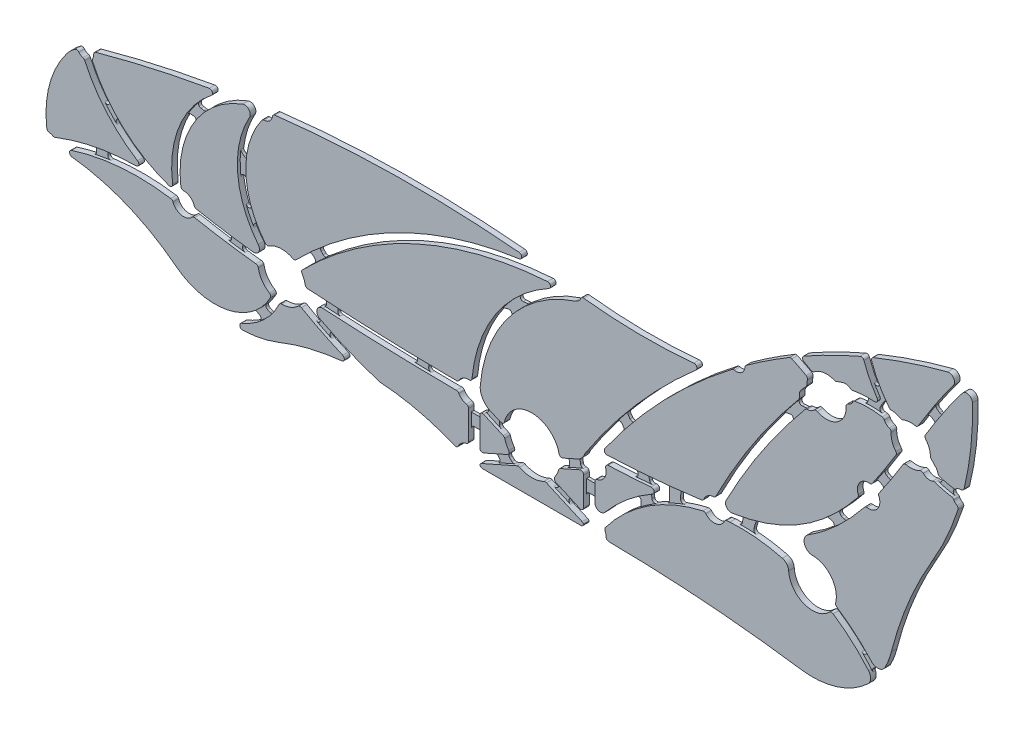
SolidWorks part; units mm, degrees
material "AR-M2"
ref_plane "正面" through (0, 0, 0) normal (0, 0, 1) x (1, 0, 0)
ref_plane "平面" through (0, 0, 0) normal (0, 1, 0) x (1, 0, 0)
ref_plane "右側面" through (0, 0, 0) normal (1, 0, 0) x (0, 0, -1)
sketch "ｽｹｯﾁ1" plane through (0, 0, 0) normal (0, 0, 1) x (1, 0, 0)
  line L1 (-22.5, -10.101) -> (-22.5, 0.101)
  line L2 (-22.5, -10.101) -> (-22.5, 0.101)
  line L3 (22.5, 0.101) -> (22.5, -6.4126)
  line L4 (22.5, 0.101) -> (22.5, -6.4126)
  line L6 (11.119, 1.5832) -> (16.2024, 3.8425)
  line L7 (18.5, -10.042) -> (18.5, 0.042)
  line L8 (8.626, -7.1923) -> (17.0939, -10.9558)
  line L9 (17.0939, 0.9558) -> (10.1663, -2.1231)
  line L10 (18.5, -10.042) -> (18.5, 0.042)
  line L11 (8.626, -7.1923) -> (17.0939, -10.9558)
  line L12 (17.0939, 0.9558) -> (10.1663, -2.1231)
  line L13 (-10.1663, -2.1231) -> (-17.0939, 0.9558)
  line L14 (-17.0939, -10.9558) -> (-8.626, -7.1923)
  line L15 (-18.5, 0.042) -> (-18.5, -10.042)
  line L16 (-10.1663, -2.1231) -> (-17.0939, 0.9558)
  line L17 (-17.0939, -10.9558) -> (-8.626, -7.1923)
  line L18 (-18.5, 0.042) -> (-18.5, -10.042)
  line L19 (-17.5, -16) -> (17.5, -16)
  line L20 (-5.2366, -8.9688) -> (-17.9339, -14.6121)
  line L21 (17.9339, -14.6121) -> (5.2366, -8.9688)
  line L22 (-17.5, -16) -> (17.5, -16)
  line L23 (-5.2366, -8.9688) -> (-17.9339, -14.6121)
  line L24 (17.9339, -14.6121) -> (5.2366, -8.9688)
  line L25 (-14.7807, 3.2107) -> (-11.119, 1.5832)
  line L26 (11.119, 1.5832) -> (16.2024, 3.8425)
  line L27 (-14.7807, 3.2107) -> (-11.119, 1.5832)
  arc A16 (-103.3566, -14.0607) -> (-89.967, -1.5631) centre (-112.8701, 9.5532) ccw
  arc A17 (-89.0603, -0.9998) -> (-89.967, -1.5631) centre (-89.0674, -1.9998) ccw
  arc A18 (-89.0603, -0.9998) -> (-83.2113, 1.2758) centre (-89, 7.5) ccw
  arc A19 (-82.0317, 1.4104) -> (-83.2113, 1.2758) centre (-82.5302, 0.5435) ccw
  arc A20 (-82.0317, 1.4104) -> (-67.3468, -5.898) centre (-13.9413, 119.818) ccw
  arc A21 (-67.6378, -7.8134) -> (-67.3468, -5.898) centre (-67.7378, -6.8184) ccw
  arc A22 (-67.6378, -7.8134) -> (-90.1176, -13.3365) centre (-59.3978, -89.8605) ccw
  arc A23 (-102.9573, -15.9879) -> (-90.1176, -13.3365) centre (-103.9017, 21) ccw
  arc A24 (-103.3566, -14.0607) -> (-102.9573, -15.9879) centre (-102.9829, -14.9883) ccw
  arc A25 (-103.3566, -14.0607) -> (-89.967, -1.5631) centre (-112.8701, 9.5532) ccw
  arc A26 (-89.0603, -0.9998) -> (-89.967, -1.5631) centre (-89.0674, -1.9998) ccw
  arc A27 (-89.0603, -0.9998) -> (-83.2113, 1.2758) centre (-89, 7.5) ccw
  arc A28 (-82.0317, 1.4104) -> (-83.2113, 1.2758) centre (-82.5302, 0.5435) ccw
  arc A29 (-82.0317, 1.4104) -> (-67.3468, -5.898) centre (-13.9413, 119.818) ccw
  arc A30 (-67.6378, -7.8134) -> (-67.3468, -5.898) centre (-67.7378, -6.8184) ccw
  arc A31 (-67.6378, -7.8134) -> (-90.1176, -13.3365) centre (-59.3978, -89.8605) ccw
  arc A32 (-102.9573, -15.9879) -> (-90.1176, -13.3365) centre (-103.9017, 21) ccw
  arc A33 (-103.3566, -14.0607) -> (-102.9573, -15.9879) centre (-102.9829, -14.9883) ccw
  arc A35 (-114.85, 52.6669) -> (-155.2686, 43.5545) centre (-42.29, -363.3692) ccw
  arc A36 (-114.0595, 50.8962) -> (-114.85, 52.6669) centre (-114.6782, 51.6818) ccw
  arc A37 (-114.0595, 50.8962) -> (-127.9008, 16.5808) centre (-91.0356, 21.6602) ccw
  arc A38 (-126.7209, -8.1253) -> (-163.7257, 7.0322) centre (-172, -65.9175) ccw
  arc A39 (-163.9203, 8.9775) -> (-163.7257, 7.0322) centre (-163.613, 8.0259) ccw
  arc A40 (-128.5572, 11.8079) -> (-163.9203, 8.9775) centre (-140.2604, -64.3004) ccw
  arc A41 (-127.7673, 11.1556) -> (-128.5572, 11.8079) centre (-128.7091, 10.8195) ccw
  arc A42 (-127.7673, 11.1556) -> (-121.0036, 9.8502) centre (-124, 12.5) ccw
  arc A43 (-120.0633, 10.1693) -> (-121.0036, 9.8502) centre (-120.2545, 9.1877) ccw
  arc A44 (-120.0633, 10.1693) -> (-98.2474, 6.8503) centre (-69.0994, 271.8045) ccw
  arc A45 (-97.3718, 6.0294) -> (-98.2474, 6.8503) centre (-98.3567, 5.8563) ccw
  arc A46 (-97.3718, 6.0294) -> (-93.4427, 0.2535) centre (-89, 7.5) ccw
  arc A47 (-93.0844, -1.0722) -> (-93.4427, 0.2535) centre (-93.9654, -0.5991) ccw
  arc A48 (-126.7209, -8.1253) -> (-93.0844, -1.0722) centre (-112.8701, 9.5532) ccw
  arc A49 (-126.7209, -8.1253) -> (-163.7257, 7.0322) centre (-172, -65.9175) ccw
  arc A50 (-163.9203, 8.9775) -> (-163.7257, 7.0322) centre (-163.613, 8.0259) ccw
  arc A51 (-128.5572, 11.8079) -> (-163.9203, 8.9775) centre (-140.2604, -64.3004) ccw
  arc A52 (-127.7673, 11.1556) -> (-128.5572, 11.8079) centre (-128.7091, 10.8195) ccw
  arc A53 (-127.7673, 11.1556) -> (-121.0036, 9.8502) centre (-124, 12.5) ccw
  arc A54 (-120.0633, 10.1693) -> (-121.0036, 9.8502) centre (-120.2545, 9.1877) ccw
  arc A55 (-120.0633, 10.1693) -> (-98.2474, 6.8503) centre (-69.0994, 271.8045) ccw
  arc A56 (-97.3718, 6.0294) -> (-98.2474, 6.8503) centre (-98.3567, 5.8563) ccw
  arc A57 (-97.3718, 6.0294) -> (-93.4427, 0.2535) centre (-89, 7.5) ccw
  arc A58 (-93.0844, -1.0722) -> (-93.4427, 0.2535) centre (-93.9654, -0.5991) ccw
  arc A59 (-126.7209, -8.1253) -> (-93.0844, -1.0722) centre (-112.8701, 9.5532) ccw
  arc A60 (-129.2172, 15.4989) -> (-127.9008, 16.5808) centre (-128.8914, 16.4443) ccw
  arc A61 (-156.4002, 40.1644) -> (-129.2172, 15.4989) centre (-114.0417, 59.5347) ccw
  arc A62 (-156.3681, 41.0602) -> (-156.4002, 40.1644) centre (-155.4908, 40.5803) ccw
  arc A63 (-156.3681, 41.0602) -> (-156.0008, 42.5682) centre (-159, 42.5) ccw
  arc A64 (-155.2686, 43.5545) -> (-156.0008, 42.5682) centre (-155.001, 42.5909) ccw
  arc A65 (-114.85, 52.6669) -> (-155.2686, 43.5545) centre (-42.29, -363.3692) ccw
  arc A66 (-114.0595, 50.8962) -> (-114.85, 52.6669) centre (-114.6782, 51.6818) ccw
  arc A67 (-114.0595, 50.8962) -> (-127.9008, 16.5808) centre (-91.0356, 21.6602) ccw
  arc A68 (-129.2172, 15.4989) -> (-127.9008, 16.5808) centre (-128.8914, 16.4443) ccw
  arc A69 (-156.4002, 40.1644) -> (-129.2172, 15.4989) centre (-114.0417, 59.5347) ccw
  arc A70 (-156.3681, 41.0602) -> (-156.4002, 40.1644) centre (-155.4908, 40.5803) ccw
  arc A71 (-156.3681, 41.0602) -> (-156.0008, 42.5682) centre (-159, 42.5) ccw
  arc A72 (-155.2686, 43.5545) -> (-156.0008, 42.5682) centre (-155.001, 42.5909) ccw
  arc A73 (-100.5051, 50.879) -> (-97.4246, 13.2154) centre (-71.0713, 34.3286) ccw
  arc A74 (-99.214, 9.978) -> (-97.4246, 13.2154) centre (-98.9855, 11.9649) ccw
  arc A75 (-4.471, 57.2503) -> (-91.4838, 56.0721) centre (-42.29, -363.3692) ccw
  arc A76 (-140.9263, 15.6997) -> (-169.717, 10.0822) centre (-140.2604, -64.3004) ccw
  arc A77 (-170.5639, 10.1339) -> (-169.717, 10.0822) centre (-170.0852, 11.0119) ccw
  arc A78 (-170.5639, 10.1339) -> (-171.786, 10.4924) centre (-172, 7.5) ccw
  arc A79 (-172.7066, 11.3632) -> (-171.786, 10.4924) centre (-171.7146, 11.4898) ccw
  arc A80 (-165.6353, 37.9447) -> (-172.7066, 11.3632) centre (-136.5587, 15.9784) ccw
  arc A81 (-162.6526, 40.7855) -> (-165.6353, 37.9447) centre (-155.4945, 30.2837) ccw
  arc A82 (-161.317, 40.5944) -> (-162.6526, 40.7855) centre (-162.0894, 39.9592) ccw
  arc A83 (-161.317, 40.5944) -> (-159.8316, 39.6176) centre (-159, 42.5) ccw
  arc A84 (-159.198, 39.0695) -> (-159.8316, 39.6176) centre (-160.1088, 38.6568) ccw
  arc A85 (-159.198, 39.0695) -> (-140.4029, 17.5466) centre (-114.0417, 59.5347) ccw
  arc A86 (-140.9263, 15.6997) -> (-140.4029, 17.5466) centre (-140.9346, 16.6997) ccw
  arc A87 (-140.9263, 15.6997) -> (-169.717, 10.0822) centre (-140.2604, -64.3004) ccw
  arc A88 (-170.5639, 10.1339) -> (-169.717, 10.0822) centre (-170.0852, 11.0119) ccw
  arc A89 (-170.5639, 10.1339) -> (-171.786, 10.4924) centre (-172, 7.5) ccw
  arc A90 (-172.7066, 11.3632) -> (-171.786, 10.4924) centre (-171.7146, 11.4898) ccw
  arc A91 (-165.6353, 37.9447) -> (-172.7066, 11.3632) centre (-136.5587, 15.9784) ccw
  arc A92 (-162.6526, 40.7855) -> (-165.6353, 37.9447) centre (-155.4945, 30.2837) ccw
  arc A93 (-161.317, 40.5944) -> (-162.6526, 40.7855) centre (-162.0894, 39.9592) ccw
  arc A94 (-161.317, 40.5944) -> (-159.8316, 39.6176) centre (-159, 42.5) ccw
  arc A95 (-159.198, 39.0695) -> (-159.8316, 39.6176) centre (-160.1088, 38.6568) ccw
  arc A96 (-159.198, 39.0695) -> (-140.4029, 17.5466) centre (-114.0417, 59.5347) ccw
  arc A97 (-140.9263, 15.6997) -> (-140.4029, 17.5466) centre (-140.9346, 16.6997) ccw
  arc A98 (-4.4224, 55.2639) -> (-4.471, 57.2503) centre (-4.5606, 56.2543) ccw
  arc A99 (-4.4224, 55.2639) -> (-83.9236, 15.238) centre (14.6672, -81.6202) ccw
  arc A100 (-85.0963, 15.0506) -> (-83.9236, 15.238) centre (-84.637, 15.9389) ccw
  arc A101 (-85.0963, 15.0506) -> (-93.5868, 14.6562) centre (-89, 7.5) ccw
  arc A102 (-94.9009, 14.8656) -> (-93.5868, 14.6562) centre (-94.1264, 15.4981) ccw
  arc A103 (-96.1287, 52.1831) -> (-94.9009, 14.8656) centre (-71.0713, 34.3286) ccw
  arc A104 (-95.319, 52.6028) -> (-96.1287, 52.1831) centre (-95.3143, 51.6028) ccw
  arc A105 (-95.319, 52.6028) -> (-92.3587, 55.2099) centre (-95.3328, 55.6027) ccw
  arc A106 (-91.4838, 56.0721) -> (-92.3587, 55.2099) centre (-91.3673, 55.0789) ccw
  arc A107 (-4.471, 57.2503) -> (-91.4838, 56.0721) centre (-42.29, -363.3692) ccw
  arc A108 (-4.4224, 55.2639) -> (-4.471, 57.2503) centre (-4.5606, 56.2543) ccw
  arc A109 (-4.4224, 55.2639) -> (-83.9236, 15.238) centre (14.6672, -81.6202) ccw
  arc A110 (-85.0963, 15.0506) -> (-83.9236, 15.238) centre (-84.637, 15.9389) ccw
  arc A111 (-85.0963, 15.0506) -> (-93.5868, 14.6562) centre (-89, 7.5) ccw
  arc A112 (-94.9009, 14.8656) -> (-93.5868, 14.6562) centre (-94.1264, 15.4981) ccw
  arc A113 (-96.1287, 52.1831) -> (-94.9009, 14.8656) centre (-71.0713, 34.3286) ccw
  arc A114 (-95.319, 52.6028) -> (-96.1287, 52.1831) centre (-95.3143, 51.6028) ccw
  arc A115 (-95.319, 52.6028) -> (-92.3587, 55.2099) centre (-95.3328, 55.6027) ccw
  arc A116 (-91.4838, 56.0721) -> (-92.3587, 55.2099) centre (-91.3673, 55.0789) ccw
  arc A117 (-22.314, 8.9957) -> (-25.9592, 7.0085) centre (-22.5, 5) ccw
  arc A118 (-26.8289, 6.5106) -> (-25.9592, 7.0085) centre (-26.824, 7.5106) ccw
  arc A119 (-79.7472, 8.3552) -> (-26.8289, 6.5106) centre (-22.5, 890.7) ccw
  arc A120 (-80.6633, 9.158) -> (-79.7472, 8.3552) centre (-79.6825, 9.3531) ccw
  arc A121 (-80.6633, 9.158) -> (-81.8017, 12.0204) centre (-89, 7.5) ccw
  arc A122 (-81.6673, 13.2539) -> (-81.8017, 12.0204) centre (-80.9548, 12.5522) ccw
  arc A123 (5.6096, 53.2849) -> (-81.6673, 13.2539) centre (14.6672, -81.6202) ccw
  arc A124 (6.1525, 51.4076) -> (5.6096, 53.2849) centre (5.6766, 52.2871) ccw
  arc A125 (6.1525, 51.4076) -> (-21.2718, 9.9017) centre (31.2679, 5) ccw
  arc A126 (-22.314, 8.9957) -> (-21.2718, 9.9017) centre (-22.2675, 9.9946) ccw
  arc A127 (-22.314, 8.9957) -> (-25.9592, 7.0085) centre (-22.5, 5) ccw
  arc A128 (-26.8289, 6.5106) -> (-25.9592, 7.0085) centre (-26.824, 7.5106) ccw
  arc A129 (-79.7472, 8.3552) -> (-26.8289, 6.5106) centre (-22.5, 890.7) ccw
  arc A130 (-80.6633, 9.158) -> (-79.7472, 8.3552) centre (-79.6825, 9.3531) ccw
  arc A131 (-80.6633, 9.158) -> (-81.8017, 12.0204) centre (-89, 7.5) ccw
  arc A132 (-81.6673, 13.2539) -> (-81.8017, 12.0204) centre (-80.9548, 12.5522) ccw
  arc A133 (5.6096, 53.2849) -> (-81.6673, 13.2539) centre (14.6672, -81.6202) ccw
  arc A134 (6.1525, 51.4076) -> (5.6096, 53.2849) centre (5.6766, 52.2871) ccw
  arc A135 (6.1525, 51.4076) -> (-21.2718, 9.9017) centre (31.2679, 5) ccw
  arc A136 (-22.314, 8.9957) -> (-21.2718, 9.9017) centre (-22.2675, 9.9946) ccw
  arc A137 (-119.4498, 13.1062) -> (-99.214, 9.978) centre (-69.0994, 271.8045) ccw
  arc A138 (-27.4366, -13.8466) -> (-54.0639, -7.5734) centre (-59.3978, -89.8605) ccw
  arc A139 (-54.3014, -7.5287) -> (-54.0639, -7.5734) centre (-53.9993, -6.5755) ccw
  arc A140 (-75.487, 1.2505) -> (-54.3014, -7.5287) centre (-13.9413, 119.818) ccw
  arc A141 (-74.4485, 5.0222) -> (-75.487, 1.2505) centre (-74.5656, 3.0256) ccw
  arc A142 (-74.4485, 5.0222) -> (-26.8313, 3.5106) centre (-22.5, 890.7) ccw
  arc A143 (-25.969, 3.0085) -> (-26.8313, 3.5106) centre (-26.8362, 2.5106) ccw
  arc A144 (-25.969, 3.0085) -> (-23.3, 1.0808) centre (-22.5, 5) ccw
  arc A145 (-22.5, 0.101) -> (-23.3, 1.0808) centre (-23.5, 0.101) ccw
  arc A146 (-23.3, -11.0808) -> (-22.5, -10.101) centre (-23.5, -10.101) ccw
  arc A147 (-23.3, -11.0808) -> (-26.1392, -13.3399) centre (-22.5, -15) ccw
  arc A148 (-27.4366, -13.8466) -> (-26.1392, -13.3399) centre (-27.049, -12.9248) ccw
  arc A149 (-27.4366, -13.8466) -> (-54.0639, -7.5734) centre (-59.3978, -89.8605) ccw
  arc A150 (-54.3014, -7.5287) -> (-54.0639, -7.5734) centre (-53.9993, -6.5755) ccw
  arc A151 (-75.487, 1.2505) -> (-54.3014, -7.5287) centre (-13.9413, 119.818) ccw
  arc A152 (-74.4485, 5.0222) -> (-75.487, 1.2505) centre (-74.5656, 3.0256) ccw
  arc A153 (-74.4485, 5.0222) -> (-26.8313, 3.5106) centre (-22.5, 890.7) ccw
  arc A154 (-25.969, 3.0085) -> (-26.8313, 3.5106) centre (-26.8362, 2.5106) ccw
  arc A155 (-25.969, 3.0085) -> (-23.3, 1.0808) centre (-22.5, 5) ccw
  arc A156 (-22.5, 0.101) -> (-23.3, 1.0808) centre (-23.5, 0.101) ccw
  arc A157 (-23.3, -11.0808) -> (-22.5, -10.101) centre (-23.5, -10.101) ccw
  arc A158 (-23.3, -11.0808) -> (-26.1392, -13.3399) centre (-22.5, -15) ccw
  arc A159 (-27.4366, -13.8466) -> (-26.1392, -13.3399) centre (-27.049, -12.9248) ccw
  arc A160 (-120.207, 13.7702) -> (-119.4498, 13.1062) centre (-119.2588, 14.0878) ccw
  arc A161 (-120.207, 13.7702) -> (-123.99, 16.5) centre (-124, 12.5) ccw
  arc A162 (-124.9796, 17.3747) -> (-123.99, 16.5) centre (-123.9875, 17.5) ccw
  arc A163 (-102.9446, 53.7342) -> (-124.9796, 17.3747) centre (-91.0356, 21.6602) ccw
  arc A164 (-100.5051, 50.879) -> (-102.9446, 53.7342) centre (-102.2484, 51.8592) ccw
  arc A165 (-100.5051, 50.879) -> (-97.4246, 13.2154) centre (-71.0713, 34.3286) ccw
  arc A166 (-99.214, 9.978) -> (-97.4246, 13.2154) centre (-98.9855, 11.9649) ccw
  arc A167 (-119.4498, 13.1062) -> (-99.214, 9.978) centre (-69.0994, 271.8045) ccw
  arc A168 (-120.207, 13.7702) -> (-119.4498, 13.1062) centre (-119.2588, 14.0878) ccw
  arc A169 (-120.207, 13.7702) -> (-123.99, 16.5) centre (-124, 12.5) ccw
  arc A170 (-124.9796, 17.3747) -> (-123.99, 16.5) centre (-123.9875, 17.5) ccw
  arc A171 (-102.9446, 53.7342) -> (-124.9796, 17.3747) centre (-91.0356, 21.6602) ccw
  arc A172 (-100.5051, 50.879) -> (-102.9446, 53.7342) centre (-102.2484, 51.8592) ccw
  arc A180 (17.0939, -10.9558) -> (18.5, -10.042) centre (17.5, -10.042) ccw
  arc A181 (8.2111, -5.7077) -> (8.626, -7.1923) centre (9.0322, -6.2785) ccw
  arc A182 (22.5, -6.4126) -> (26.0294, -7.7013) centre (24.5, -6.4126) ccw
  arc A183 (23.3, 1.0808) -> (22.5, 0.101) centre (23.5, 0.101) ccw
  arc A184 (23.3, 1.0808) -> (26.3403, 6.1191) centre (22.5, 5) ccw
  arc A185 (27.2601, 7.398) -> (26.3403, 6.1191) centre (27.3003, 6.3988) ccw
  arc A186 (27.2601, 7.398) -> (42.5161, 8.3479) centre (13.2682, 355.1295) ccw
  arc A187 (43.0938, 6.4818) -> (42.5161, 8.3479) centre (42.6001, 7.3514) ccw
  arc A188 (107.7452, 73.9205) -> (100.6016, 72.9268) centre (105, 67.4812) ccw
  arc A189 (99.4771, 72.8365) -> (100.6016, 72.9268) centre (99.9733, 73.7047) ccw
  arc A190 (99.4771, 72.8365) -> (96.9768, 74.198) centre (65, 12.5) ccw
  arc A191 (96.9469, 75.9576) -> (96.9768, 74.198) centre (97.4369, 75.0859) ccw
  arc A192 (116.993, 85.9037) -> (96.9469, 75.9576) centre (203.2901, -113.1988) ccw
  arc A193 (118.3344, 85.3171) -> (116.993, 85.9037) centre (117.3907, 84.9862) ccw
  arc A194 (118.3344, 85.3171) -> (122.9876, 76.0572) centre (156.5, 98.6967) ccw
  arc A195 (122.0896, 74.4999) -> (122.9876, 76.0572) centre (122.1589, 75.4974) ccw
  arc A196 (122.0896, 74.4999) -> (114.3306, 74.0344) centre (120, 44.4324) ccw
  arc A197 (113.5331, 74.2236) -> (114.3306, 74.0344) centre (114.1425, 75.0165) ccw
  arc A198 (113.5331, 74.2236) -> (110.8362, 74.7163) centre (111.7051, 71.8449) ccw
  arc A199 (110.8362, 74.7163) -> (108.5008, 73.9088) centre (120, 44.4324) ccw
  arc A200 (107.7452, 73.9205) -> (108.5008, 73.9088) centre (108.1373, 74.8404) ccw
  arc A201 (107.7452, 73.9205) -> (100.6016, 72.9268) centre (105, 67.4812) ccw
  arc A202 (99.4771, 72.8365) -> (100.6016, 72.9268) centre (99.9733, 73.7047) ccw
  arc A203 (99.4771, 72.8365) -> (96.9768, 74.198) centre (65, 12.5) ccw
  arc A204 (96.9469, 75.9576) -> (96.9768, 74.198) centre (97.4369, 75.0859) ccw
  arc A205 (116.993, 85.9037) -> (96.9469, 75.9576) centre (203.2901, -113.1988) ccw
  arc A206 (118.3344, 85.3171) -> (116.993, 85.9037) centre (117.3907, 84.9862) ccw
  arc A207 (118.3344, 85.3171) -> (122.9876, 76.0572) centre (156.5, 98.6967) ccw
  arc A208 (122.0896, 74.4999) -> (122.9876, 76.0572) centre (122.1589, 75.4974) ccw
  arc A209 (122.0896, 74.4999) -> (114.3306, 74.0344) centre (120, 44.4324) ccw
  arc A210 (113.5331, 74.2236) -> (114.3306, 74.0344) centre (114.1425, 75.0165) ccw
  arc A211 (113.5331, 74.2236) -> (110.8362, 74.7163) centre (111.7051, 71.8449) ccw
  arc A212 (110.8362, 74.7163) -> (108.5008, 73.9088) centre (120, 44.4324) ccw
  arc A213 (107.7452, 73.9205) -> (108.5008, 73.9088) centre (108.1373, 74.8404) ccw
  arc A214 (43.0938, 6.4818) -> (26.0294, -7.7013) centre (74.1755, -48.2713) ccw
  arc A215 (22.5, -6.4126) -> (26.0294, -7.7013) centre (24.5, -6.4126) ccw
  arc A216 (23.3, 1.0808) -> (22.5, 0.101) centre (23.5, 0.101) ccw
  arc A217 (23.3, 1.0808) -> (26.3403, 6.1191) centre (22.5, 5) ccw
  arc A218 (89.2736, 9.7568) -> (70.6226, 11.5834) centre (74.1755, -48.2713) ccw
  arc A219 (91.5134, 7.0221) -> (89.2736, 9.7568) centre (88.5182, 6.8535) ccw
  arc A220 (91.5134, 7.0221) -> (106.0705, 1.5503) centre (100, 7.5) ccw
  arc A221 (107.3377, 1.6835) -> (106.0705, 1.5503) centre (106.7847, 0.8503) ccw
  arc A222 (120.0008, -9.6028) -> (107.3377, 1.6835) centre (74.1755, -48.2713) ccw
  arc A223 (119.7512, -13.7341) -> (120.0008, -9.6028) centre (117.708, -11.5375) ccw
  arc A224 (95.9045, -21.2094) -> (119.7512, -13.7341) centre (100, 7.5) ccw
  arc A225 (95.9045, -21.2094) -> (27.4903, -16.024) centre (22.5, -535.7727) ccw
  arc A226 (26.5, -15.0192) -> (27.4903, -16.024) centre (27.4999, -15.024) ccw
  arc A227 (26.5, -15.0192) -> (26.1198, -13.2978) centre (22.5, -15) ccw
  arc A228 (26.225, -12.2719) -> (26.1198, -13.2978) centre (27.0247, -12.8723) ccw
  arc A229 (60.9851, 10.2199) -> (26.225, -12.2719) centre (74.1755, -48.2713) ccw
  arc A230 (61.9641, 9.8955) -> (60.9851, 10.2199) centre (61.2051, 9.2444) ccw
  arc A231 (61.9641, 9.8955) -> (68.6438, 10.85) centre (65, 12.5) ccw
  arc A232 (69.4318, 11.4299) -> (68.6438, 10.85) centre (69.5548, 10.4374) ccw
  arc A233 (69.4318, 11.4299) -> (70.5449, 11.5758) centre (59.6347, 90.4932) ccw
  arc A234 (70.6226, 11.5834) -> (70.5449, 11.5758) centre (70.6819, 10.5852) ccw
  arc A235 (89.2736, 9.7568) -> (70.6226, 11.5834) centre (74.1755, -48.2713) ccw
  arc A236 (91.5134, 7.0221) -> (89.2736, 9.7568) centre (88.5182, 6.8535) ccw
  arc A237 (91.5134, 7.0221) -> (106.0705, 1.5503) centre (100, 7.5) ccw
  arc A238 (107.3377, 1.6835) -> (106.0705, 1.5503) centre (106.7847, 0.8503) ccw
  arc A239 (120.0008, -9.6028) -> (107.3377, 1.6835) centre (74.1755, -48.2713) ccw
  arc A240 (119.7512, -13.7341) -> (120.0008, -9.6028) centre (117.708, -11.5375) ccw
  arc A241 (95.9045, -21.2094) -> (119.7512, -13.7341) centre (100, 7.5) ccw
  arc A242 (95.9045, -21.2094) -> (27.4903, -16.024) centre (22.5, -535.7727) ccw
  arc A243 (26.5, -15.0192) -> (27.4903, -16.024) centre (27.4999, -15.024) ccw
  arc A244 (26.5, -15.0192) -> (26.1198, -13.2978) centre (22.5, -15) ccw
  arc A245 (26.225, -12.2719) -> (26.1198, -13.2978) centre (27.0247, -12.8723) ccw
  arc A246 (60.9851, 10.2199) -> (26.225, -12.2719) centre (74.1755, -48.2713) ccw
  arc A247 (61.9641, 9.8955) -> (60.9851, 10.2199) centre (61.2051, 9.2444) ccw
  arc A248 (61.9641, 9.8955) -> (68.6438, 10.85) centre (65, 12.5) ccw
  arc A249 (69.4318, 11.4299) -> (68.6438, 10.85) centre (69.5548, 10.4374) ccw
  arc A250 (69.4318, 11.4299) -> (70.5449, 11.5758) centre (59.6347, 90.4932) ccw
  arc A251 (70.6226, 11.5834) -> (70.5449, 11.5758) centre (70.6819, 10.5852) ccw
  arc A252 (27.2601, 7.398) -> (26.3403, 6.1191) centre (27.3003, 6.3988) ccw
  arc A253 (27.2601, 7.398) -> (42.5161, 8.3479) centre (13.2682, 355.1295) ccw
  arc A254 (71.3431, 59.0772) -> (26.022, 11.9612) centre (203.2901, -113.1988) ccw
  arc A255 (72.1979, 59.2524) -> (71.3431, 59.0772) centre (71.9512, 58.2833) ccw
  arc A256 (72.1979, 59.2524) -> (75.9352, 62.0305) centre (72.938, 62.1596) ccw
  arc A257 (76.3493, 62.7985) -> (75.9352, 62.0305) centre (76.9343, 61.9874) ccw
  arc A258 (91.7165, 72.9204) -> (76.3493, 62.7985) centre (203.2901, -113.1988) ccw
  arc A259 (92.6465, 72.9722) -> (91.7165, 72.9204) centre (92.2307, 72.0627) ccw
  arc A260 (97.7506, 70.3671) -> (92.6465, 72.9722) centre (65, 12.5) ccw
  arc A261 (98.2258, 69.2449) -> (97.7506, 70.3671) centre (97.2581, 69.4969) ccw
  arc A262 (98.2258, 69.2449) -> (98.0007, 67.5789) centre (105, 67.4812) ccw
  arc A263 (97.7054, 66.8832) -> (98.0007, 67.5789) centre (97.0008, 67.5928) ccw
  arc A264 (97.7054, 66.8832) -> (96.0213, 65.0748) centre (120, 44.4324) ccw
  arc A265 (96.0213, 65.0748) -> (95.3497, 62.5466) centre (98.2949, 63.1176) ccw
  arc A266 (95.1344, 61.7139) -> (95.3497, 62.5466) centre (94.368, 62.3562) ccw
  arc A267 (95.1344, 61.7139) -> (65.5834, 17.0366) centre (276.8279, -90.5756) ccw
  arc A268 (64.7539, 16.4924) -> (65.5834, 17.0366) centre (64.6924, 17.4905) ccw
  arc A269 (64.7539, 16.4924) -> (61.2853, 13.9837) centre (65, 12.5) ccw
  arc A270 (60.4936, 13.364) -> (61.2853, 13.9837) centre (60.3567, 14.3546) ccw
  arc A271 (26.8783, 10.3852) -> (60.4936, 13.364) centre (13.2682, 355.1295) ccw
  arc A272 (26.022, 11.9612) -> (26.8783, 10.3852) centre (26.8389, 11.3844) ccw
  arc A273 (71.3431, 59.0772) -> (26.022, 11.9612) centre (203.2901, -113.1988) ccw
  arc A274 (72.1979, 59.2524) -> (71.3431, 59.0772) centre (71.9512, 58.2833) ccw
  arc A275 (72.1979, 59.2524) -> (75.9352, 62.0305) centre (72.938, 62.1596) ccw
  arc A276 (76.3493, 62.7985) -> (75.9352, 62.0305) centre (76.9343, 61.9874) ccw
  arc A277 (91.7165, 72.9204) -> (76.3493, 62.7985) centre (203.2901, -113.1988) ccw
  arc A278 (92.6465, 72.9722) -> (91.7165, 72.9204) centre (92.2307, 72.0627) ccw
  arc A279 (97.7506, 70.3671) -> (92.6465, 72.9722) centre (65, 12.5) ccw
  arc A280 (98.2258, 69.2449) -> (97.7506, 70.3671) centre (97.2581, 69.4969) ccw
  arc A281 (98.2258, 69.2449) -> (98.0007, 67.5789) centre (105, 67.4812) ccw
  arc A282 (97.7054, 66.8832) -> (98.0007, 67.5789) centre (97.0008, 67.5928) ccw
  arc A283 (97.7054, 66.8832) -> (96.0213, 65.0748) centre (120, 44.4324) ccw
  arc A284 (96.0213, 65.0748) -> (95.3497, 62.5466) centre (98.2949, 63.1176) ccw
  arc A285 (95.1344, 61.7139) -> (95.3497, 62.5466) centre (94.368, 62.3562) ccw
  arc A286 (95.1344, 61.7139) -> (65.5834, 17.0366) centre (276.8279, -90.5756) ccw
  arc A287 (64.7539, 16.4924) -> (65.5834, 17.0366) centre (64.6924, 17.4905) ccw
  arc A288 (64.7539, 16.4924) -> (61.2853, 13.9837) centre (65, 12.5) ccw
  arc A289 (60.4936, 13.364) -> (61.2853, 13.9837) centre (60.3567, 14.3546) ccw
  arc A290 (26.8783, 10.3852) -> (60.4936, 13.364) centre (13.2682, 355.1295) ccw
  arc A291 (26.022, 11.9612) -> (26.8783, 10.3852) centre (26.8389, 11.3844) ccw
  arc A292 (43.0938, 6.4818) -> (42.5161, 8.3479) centre (42.6001, 7.3514) ccw
  arc A293 (43.0938, 6.4818) -> (26.0294, -7.7013) centre (74.1755, -48.2713) ccw
  arc A294 (8.2111, -5.7077) -> (9.6113, -2.7608) centre (0, 0) ccw
  arc A295 (10.1663, -2.1231) -> (9.6113, -2.7608) centre (10.5725, -3.0369) ccw
  arc A296 (18.5, 0.042) -> (17.0939, 0.9558) centre (17.5, 0.042) ccw
  arc A297 (148.0871, 96.6622) -> (121.6343, 87.8518) centre (203.2901, -113.1988) ccw
  arc A298 (150.1845, 93.5129) -> (148.0871, 96.6622) centre (148.5959, 94.728) ccw
  arc A302 (136.5337, 74.3112) -> (137.605, 74.7637) centre (136.7528, 75.2869) ccw
  arc A303 (136.5337, 74.3112) -> (132.2548, 73.9205) centre (135, 67.4812) ccw
  arc A304 (131.4992, 73.9088) -> (132.2548, 73.9205) centre (131.8627, 74.8404) ccw
  arc A305 (131.4992, 73.9088) -> (129.1638, 74.7163) centre (120, 44.4324) ccw
  arc A306 (129.1638, 74.7163) -> (128.1602, 74.8418) centre (128.2949, 71.8449) ccw
  arc A307 (127.3364, 75.2137) -> (128.1602, 74.8418) centre (128.1152, 75.8408) ccw
  arc A308 (69.2612, 17.6244) -> (71.3386, 14.7231) centre (71.0347, 16.6999) ccw
  arc A309 (97.4124, 59.7615) -> (69.2612, 17.6244) centre (276.8279, -90.5756) ccw
  arc A310 (98.2079, 60.1189) -> (97.4124, 59.7615) centre (98.1789, 59.1193) ccw
  arc A311 (98.2079, 60.1189) -> (100.5079, 61.0921) centre (98.2949, 63.1176) ccw
  arc A312 (101.7149, 61.3) -> (100.5079, 61.0921) centre (101.2456, 60.4169) ccw
  arc A313 (101.7149, 61.3) -> (111.9821, 67.9818) centre (105, 67.4812) ccw
  arc A314 (112.6609, 69.0012) -> (111.9821, 67.9818) centre (112.9795, 68.0533) ccw
  arc A315 (112.6609, 69.0012) -> (114.4231, 70.575) centre (111.7051, 71.8449) ccw
  arc A316 (115.1504, 71.1356) -> (114.4231, 70.575) centre (115.3291, 70.1517) ccw
  arc A317 (124.8496, 71.1356) -> (115.1504, 71.1356) centre (120, 44.4324) ccw
  arc A318 (125.5769, 70.575) -> (124.8496, 71.1356) centre (124.6709, 70.1517) ccw
  arc A319 (125.5769, 70.575) -> (127.3391, 69.0012) centre (128.2949, 71.8449) ccw
  arc A320 (128.0179, 67.9818) -> (127.3391, 69.0012) centre (127.0205, 68.0533) ccw
  arc A321 (128.0179, 67.9818) -> (129.6405, 62.9784) centre (135, 67.4812) ccw
  arc A322 (129.7265, 61.811) -> (129.6405, 62.9784) centre (128.8749, 62.3351) ccw
  arc A323 (120.3745, 48.4148) -> (121.2864, 48.8356) centre (120.4681, 49.4104) ccw
  arc A324 (120.3745, 48.4148) -> (116.2864, 42.9461) centre (120, 44.4324) ccw
  arc A325 (116.1386, 41.9495) -> (116.2864, 42.9461) centre (115.358, 42.5745) ccw
  arc A326 (69.2612, 17.6244) -> (71.3386, 14.7231) centre (71.0347, 16.6999) ccw
  arc A327 (97.4124, 59.7615) -> (69.2612, 17.6244) centre (276.8279, -90.5756) ccw
  arc A328 (98.2079, 60.1189) -> (97.4124, 59.7615) centre (98.1789, 59.1193) ccw
  arc A329 (98.2079, 60.1189) -> (100.5079, 61.0921) centre (98.2949, 63.1176) ccw
  arc A330 (101.7149, 61.3) -> (100.5079, 61.0921) centre (101.2456, 60.4169) ccw
  arc A331 (101.7149, 61.3) -> (111.9821, 67.9818) centre (105, 67.4812) ccw
  arc A332 (112.6609, 69.0012) -> (111.9821, 67.9818) centre (112.9795, 68.0533) ccw
  arc A333 (112.6609, 69.0012) -> (114.4231, 70.575) centre (111.7051, 71.8449) ccw
  arc A334 (115.1504, 71.1356) -> (114.4231, 70.575) centre (115.3291, 70.1517) ccw
  arc A335 (124.8496, 71.1356) -> (115.1504, 71.1356) centre (120, 44.4324) ccw
  arc A336 (125.5769, 70.575) -> (124.8496, 71.1356) centre (124.6709, 70.1517) ccw
  arc A337 (125.5769, 70.575) -> (127.3391, 69.0012) centre (128.2949, 71.8449) ccw
  arc A338 (128.0179, 67.9818) -> (127.3391, 69.0012) centre (127.0205, 68.0533) ccw
  arc A339 (128.0179, 67.9818) -> (129.6405, 62.9784) centre (135, 67.4812) ccw
  arc A340 (129.7265, 61.811) -> (129.6405, 62.9784) centre (128.8749, 62.3351) ccw
  arc A341 (120.3745, 48.4148) -> (121.2864, 48.8356) centre (120.4681, 49.4104) ccw
  arc A342 (120.3745, 48.4148) -> (116.2864, 42.9461) centre (120, 44.4324) ccw
  arc A343 (116.1386, 41.9495) -> (116.2864, 42.9461) centre (115.358, 42.5745) ccw
  arc A344 (121.0642, 86.6023) -> (127.3364, 75.2137) centre (156.5, 98.6967) ccw
  arc A345 (121.6343, 87.8518) -> (121.0642, 86.6023) centre (122.0106, 86.9253) ccw
  arc A346 (148.0871, 96.6622) -> (121.6343, 87.8518) centre (203.2901, -113.1988) ccw
  arc A347 (150.1845, 93.5129) -> (148.0871, 96.6622) centre (148.5959, 94.728) ccw
  arc A348 (136.5337, 74.3112) -> (137.605, 74.7637) centre (136.7528, 75.2869) ccw
  arc A349 (136.5337, 74.3112) -> (132.2548, 73.9205) centre (135, 67.4812) ccw
  arc A350 (131.4992, 73.9088) -> (132.2548, 73.9205) centre (131.8627, 74.8404) ccw
  arc A351 (131.4992, 73.9088) -> (129.1638, 74.7163) centre (120, 44.4324) ccw
  arc A352 (129.1638, 74.7163) -> (128.1602, 74.8418) centre (128.2949, 71.8449) ccw
  arc A353 (127.3364, 75.2137) -> (128.1602, 74.8418) centre (128.1152, 75.8408) ccw
  arc A354 (121.0642, 86.6023) -> (127.3364, 75.2137) centre (156.5, 98.6967) ccw
  arc A355 (121.6343, 87.8518) -> (121.0642, 86.6023) centre (122.0106, 86.9253) ccw
  arc A356 (17.0939, -10.9558) -> (18.5, -10.042) centre (17.5, -10.042) ccw
  arc A357 (8.2111, -5.7077) -> (8.626, -7.1923) centre (9.0322, -6.2785) ccw
  arc A358 (8.2111, -5.7077) -> (9.6113, -2.7608) centre (0, 0) ccw
  arc A359 (10.1663, -2.1231) -> (9.6113, -2.7608) centre (10.5725, -3.0369) ccw
  arc A360 (18.5, 0.042) -> (17.0939, 0.9558) centre (17.5, 0.042) ccw
  arc A361 (-9.6113, -2.7608) -> (-10.1663, -2.1231) centre (-10.5725, -3.0369) ccw
  arc A362 (-9.6113, -2.7608) -> (-8.2111, -5.7077) centre (0, 0) ccw
  arc A363 (-8.626, -7.1923) -> (-8.2111, -5.7077) centre (-9.0322, -6.2785) ccw
  arc A364 (-18.5, -10.042) -> (-17.0939, -10.9558) centre (-17.5, -10.042) ccw
  arc A365 (-17.0939, 0.9558) -> (-18.5, 0.042) centre (-17.5, 0.042) ccw
  arc A366 (-9.6113, -2.7608) -> (-10.1663, -2.1231) centre (-10.5725, -3.0369) ccw
  arc A367 (-9.6113, -2.7608) -> (-8.2111, -5.7077) centre (0, 0) ccw
  arc A368 (-8.626, -7.1923) -> (-8.2111, -5.7077) centre (-9.0322, -6.2785) ccw
  arc A369 (-18.5, -10.042) -> (-17.0939, -10.9558) centre (-17.5, -10.042) ccw
  arc A370 (-17.0939, 0.9558) -> (-18.5, 0.042) centre (-17.5, 0.042) ccw
  circle A371 centre (72.938, 62.1596) radius 1.6
  circle A372 centre (72.938, 62.1596) radius 1.6 construction
  arc A373 (18.4772, -15.2121) -> (17.9339, -14.6121) centre (17.5277, -15.5259) ccw
  arc A374 (17.5, -16) -> (18.4772, -15.2121) centre (17.5, -15) ccw
  arc A375 (-18.4772, -15.2121) -> (-17.5, -16) centre (-17.5, -15) ccw
  arc A376 (-17.9339, -14.6121) -> (-18.4772, -15.2121) centre (-17.5277, -15.5259) ccw
  arc A377 (-4.3913, -8.9842) -> (-5.2366, -8.9688) centre (-4.8304, -9.8827) ccw
  arc A378 (-4.3913, -8.9842) -> (4.3913, -8.9842) centre (0, 0) ccw
  arc A379 (5.2366, -8.9688) -> (4.3913, -8.9842) centre (4.8304, -9.8827) ccw
  arc A380 (18.4772, -15.2121) -> (17.9339, -14.6121) centre (17.5277, -15.5259) ccw
  arc A381 (17.5, -16) -> (18.4772, -15.2121) centre (17.5, -15) ccw
  arc A382 (-18.4772, -15.2121) -> (-17.5, -16) centre (-17.5, -15) ccw
  arc A383 (-17.9339, -14.6121) -> (-18.4772, -15.2121) centre (-17.5277, -15.5259) ccw
  arc A384 (-4.3913, -8.9842) -> (-5.2366, -8.9688) centre (-4.8304, -9.8827) ccw
  arc A385 (-4.3913, -8.9842) -> (4.3913, -8.9842) centre (0, 0) ccw
  arc A386 (5.2366, -8.9688) -> (4.3913, -8.9842) centre (4.8304, -9.8827) ccw
  arc A392 (15.611, 52.2409) -> (17.4557, 53.9822) centre (14.6672, 55.0886) ccw
  arc A393 (18.4998, 54.6068) -> (17.4557, 53.9822) centre (18.3852, 53.6134) ccw
  arc A394 (18.4998, 54.6068) -> (57.7478, 54.1867) centre (40.1338, 242.1889) ccw
  arc A395 (58.4992, 52.4382) -> (57.7478, 54.1867) centre (57.841, 53.1911) ccw
  arc A396 (58.4992, 52.4382) -> (19.152, 7.1889) centre (203.2901, -113.1988) ccw
  arc A397 (19.152, 7.1889) -> (18.7985, 6.5163) centre (22.5, 5) ccw
  arc A398 (16.2024, 3.8425) -> (18.7985, 6.5163) centre (14.1717, 8.4116) ccw
  arc A399 (9.7389, 2.27) -> (11.119, 1.5832) centre (10.7128, 2.4971) ccw
  arc A400 (9.7389, 2.27) -> (-9.7389, 2.27) centre (0, 0) ccw
  arc A401 (-11.119, 1.5832) -> (-9.7389, 2.27) centre (-10.7128, 2.4971) ccw
  arc A402 (-18.3225, 9.1999) -> (-14.7807, 3.2107) centre (-12.3439, 8.6935) ccw
  arc A403 (15.611, 52.2409) -> (-18.3225, 9.1999) centre (31.2679, 5) ccw
  arc A404 (15.611, 52.2409) -> (17.4557, 53.9822) centre (14.6672, 55.0886) ccw
  arc A405 (18.4998, 54.6068) -> (17.4557, 53.9822) centre (18.3852, 53.6134) ccw
  arc A406 (18.4998, 54.6068) -> (57.7478, 54.1867) centre (40.1338, 242.1889) ccw
  arc A407 (58.4992, 52.4382) -> (57.7478, 54.1867) centre (57.841, 53.1911) ccw
  arc A408 (58.4992, 52.4382) -> (19.152, 7.1889) centre (203.2901, -113.1988) ccw
  arc A409 (19.152, 7.1889) -> (18.7985, 6.5163) centre (22.5, 5) ccw
  arc A410 (16.2024, 3.8425) -> (18.7985, 6.5163) centre (14.1717, 8.4116) ccw
  arc A411 (9.7389, 2.27) -> (11.119, 1.5832) centre (10.7128, 2.4971) ccw
  arc A412 (9.7389, 2.27) -> (-9.7389, 2.27) centre (0, 0) ccw
  arc A413 (-11.119, 1.5832) -> (-9.7389, 2.27) centre (-10.7128, 2.4971) ccw
  arc A414 (-18.3225, 9.1999) -> (-14.7807, 3.2107) centre (-12.3439, 8.6935) ccw
  arc A415 (15.611, 52.2409) -> (-18.3225, 9.1999) centre (31.2679, 5) ccw
  arc A416 (153.9743, 63.4967) -> (156.9544, 91.5668) centre (52.35, 88.479) ccw
  arc A417 (152.9962, 62.7355) -> (153.9743, 63.4967) centre (153.0032, 63.7354) ccw
  arc A418 (152.9962, 62.7355) -> (151.0229, 62.0134) centre (152.9752, 59.7355) ccw
  arc A419 (150.204, 61.7869) -> (151.0229, 62.0134) centre (150.3722, 62.7727) ccw
  arc A420 (145.3266, 62.9598) -> (150.204, 61.7869) centre (156.5, 98.6967) ccw
  arc A421 (144.645, 63.7151) -> (145.3266, 62.9598) centre (145.625, 63.9142) ccw
  arc A422 (144.645, 63.7151) -> (143.9787, 65.0748) centre (141.7051, 63.1176) ccw
  arc A423 (143.9787, 65.0748) -> (142.2946, 66.8832) centre (120, 44.4324) ccw
  arc A424 (141.9993, 67.5789) -> (142.2946, 66.8832) centre (142.9992, 67.5928) ccw
  arc A425 (141.9993, 67.5789) -> (140.2901, 72.0654) centre (135, 67.4812) ccw
  arc A426 (140.1936, 73.2435) -> (140.2901, 72.0654) centre (141.0458, 72.7203) ccw
  arc A427 (156.9544, 91.5668) -> (153.3792, 92.7391) centre (154.9553, 91.5078) ccw
  arc A428 (153.9743, 63.4967) -> (156.9544, 91.5668) centre (52.35, 88.479) ccw
  arc A429 (152.9962, 62.7355) -> (153.9743, 63.4967) centre (153.0032, 63.7354) ccw
  arc A430 (152.9962, 62.7355) -> (151.0229, 62.0134) centre (152.9752, 59.7355) ccw
  arc A431 (150.204, 61.7869) -> (151.0229, 62.0134) centre (150.3722, 62.7727) ccw
  arc A432 (145.3266, 62.9598) -> (150.204, 61.7869) centre (156.5, 98.6967) ccw
  arc A433 (144.645, 63.7151) -> (145.3266, 62.9598) centre (145.625, 63.9142) ccw
  arc A434 (144.645, 63.7151) -> (143.9787, 65.0748) centre (141.7051, 63.1176) ccw
  arc A435 (143.9787, 65.0748) -> (142.2946, 66.8832) centre (120, 44.4324) ccw
  arc A436 (141.9993, 67.5789) -> (142.2946, 66.8832) centre (142.9992, 67.5928) ccw
  arc A437 (141.9993, 67.5789) -> (140.2901, 72.0654) centre (135, 67.4812) ccw
  arc A438 (140.1936, 73.2435) -> (140.2901, 72.0654) centre (141.0458, 72.7203) ccw
  arc A439 (156.9544, 91.5668) -> (153.3792, 92.7391) centre (154.9553, 91.5078) ccw
  arc A448 (143.571, 60.3761) -> (149.6129, 58.8445) centre (156.5, 98.6967) ccw
  arc A449 (150.3258, 58.3282) -> (149.6129, 58.8445) centre (149.4426, 57.8591) ccw
  arc A450 (150.3258, 58.3282) -> (151.4085, 57.1771) centre (152.9752, 59.7355) ccw
  arc A451 (151.8369, 56.0141) -> (151.4085, 57.1771) centre (150.8863, 56.3243) ccw
  arc A452 (142.5363, 35.3937) -> (151.8369, 56.0141) centre (52.35, 88.479) ccw
  arc A453 (142.5363, 35.3937) -> (128.1038, 0.346) centre (258.447, -32.8336) ccw
  arc A454 (125.9109, -5.5239) -> (128.1038, 0.346) centre (100, 7.5) ccw
  arc A455 (120.9994, -6.1821) -> (125.9109, -5.5239) centre (123.2305, -4.1766) ccw
  arc A456 (120.9994, -6.1821) -> (108.6769, 4.3939) centre (74.1755, -48.2713) ccw
  arc A457 (108.2539, 5.4693) -> (108.6769, 4.3939) centre (109.2249, 5.2304) ccw
  arc A463 (108.2539, 5.4693) -> (100.0042, 16) centre (100, 7.5) ccw
  arc A464 (98.4004, 21.5344) -> (100.0042, 16) centre (100.0057, 19) ccw
  arc A465 (119.4311, 40.473) -> (118.5081, 40.108) centre (119.2889, 39.4832) ccw
  arc A466 (119.4311, 40.473) -> (123.6365, 46.0984) centre (120, 44.4324) ccw
  arc A467 (123.7275, 47.0899) -> (123.6365, 46.0984) centre (124.5457, 46.5149) ccw
  arc A468 (133.3619, 60.6756) -> (132.2763, 60.2275) centre (133.1279, 59.7034) ccw
  arc A469 (133.3619, 60.6756) -> (138.2851, 61.3) centre (135, 67.4812) ccw
  arc A470 (139.4921, 61.0921) -> (138.2851, 61.3) centre (138.7544, 60.4169) ccw
  arc A471 (139.4921, 61.0921) -> (142.8648, 60.3508) centre (141.7051, 63.1176) ccw
  arc A472 (143.571, 60.3761) -> (142.8648, 60.3508) centre (143.2514, 59.4285) ccw
  arc A473 (143.571, 60.3761) -> (149.6129, 58.8445) centre (156.5, 98.6967) ccw
  arc A474 (150.3258, 58.3282) -> (149.6129, 58.8445) centre (149.4426, 57.8591) ccw
  arc A475 (150.3258, 58.3282) -> (151.4085, 57.1771) centre (152.9752, 59.7355) ccw
  arc A476 (151.8369, 56.0141) -> (151.4085, 57.1771) centre (150.8863, 56.3243) ccw
  arc A477 (142.5363, 35.3937) -> (151.8369, 56.0141) centre (52.35, 88.479) ccw
  arc A478 (142.5363, 35.3937) -> (128.1038, 0.346) centre (258.447, -32.8336) ccw
  arc A479 (125.9109, -5.5239) -> (128.1038, 0.346) centre (100, 7.5) ccw
  arc A480 (120.9994, -6.1821) -> (125.9109, -5.5239) centre (123.2305, -4.1766) ccw
  arc A481 (120.9994, -6.1821) -> (108.6769, 4.3939) centre (74.1755, -48.2713) ccw
  arc A482 (108.2539, 5.4693) -> (108.6769, 4.3939) centre (109.2249, 5.2304) ccw
  arc A483 (108.2539, 5.4693) -> (100.0042, 16) centre (100, 7.5) ccw
  arc A484 (98.4004, 21.5344) -> (100.0042, 16) centre (100.0057, 19) ccw
  arc A485 (119.4311, 40.473) -> (118.5081, 40.108) centre (119.2889, 39.4832) ccw
  arc A486 (119.4311, 40.473) -> (123.6365, 46.0984) centre (120, 44.4324) ccw
  arc A487 (123.7275, 47.0899) -> (123.6365, 46.0984) centre (124.5457, 46.5149) ccw
  arc A488 (133.3619, 60.6756) -> (132.2763, 60.2275) centre (133.1279, 59.7034) ccw
  arc A489 (133.3619, 60.6756) -> (138.2851, 61.3) centre (135, 67.4812) ccw
  arc A490 (139.4921, 61.0921) -> (138.2851, 61.3) centre (138.7544, 60.4169) ccw
  arc A491 (139.4921, 61.0921) -> (142.8648, 60.3508) centre (141.7051, 63.1176) ccw
  arc A492 (143.571, 60.3761) -> (142.8648, 60.3508) centre (143.2514, 59.4285) ccw
  spline S1 degree 3 poles (-2133.6719, 2010.1434) (110.9423, -268.7952) (19.5074, 175.9248) (397.4673, 211.1329) (2745.2271, -1387.4869) knots -3.201479 -3.201479 -3.201479 -3.201479 0.176345 3.181556 3.181556 3.181556 3.181556 only from (137.605, 74.7637) to (150.1845, 93.5129)
  spline S2 degree 3 poles (-2172.75, 1962.562) (-56.8263, -109.1453) (174.9064, -0.2396) (233.8819, 369.8799) (2539.3799, -1691.09) knots -2.708995 -2.708995 -2.708995 -2.708995 0.457359 3.759996 3.759996 3.759996 3.759996 only from (121.2864, 48.8356) to (129.7265, 61.811)
  spline S3 degree 3 poles (-2928.1118, 41.0726) (-107.7183, 59.4395) (14.8549, 3.541) (76.6227, 15.6832) (80.8013, 16.7781) (86.0872, 18.5273) (92.1873, 21.2284) (98.7972, 25.2089) (104.7931, 29.8482) (215.3446, 135.2385) (66.0453, 532.5137) (2524.5855, -1703.8454) knots -0.681883 -0.681883 -0.681883 -0.681883 0.547368 0.578095 0.608822 0.63955 0.701004 0.762459 0.823914 0.885368 4.486558 4.486558 4.486558 4.486558 only from (71.3386, 14.7231) to (116.1386, 41.9495)
  spline S4 degree 3 poles (121.2864, 48.8356) (123.8286, 52.4547) (126.6263, 56.7927) (129.3638, 61.2216) (129.7265, 61.811) knots 0.352704 0.352704 0.352704 0.352704 0.457359 0.473383 0.473383 0.473383 0.473383
  spline S5 degree 3 poles (71.3386, 14.7231) (71.6186, 14.7662) (73.4114, 15.0519) (76.6227, 15.6832) (80.8013, 16.7781) (86.0872, 18.5273) (92.1873, 21.2284) (98.7972, 25.2089) (104.7931, 29.8482) (110.6037, 35.3875) (114.2431, 39.5824) (116.1386, 41.9495) knots 0.541717 0.541717 0.541717 0.541717 0.547368 0.578095 0.608822 0.63955 0.701004 0.762459 0.823914 0.885368 0.958198 0.958198 0.958198 0.958198
  spline S6 degree 3 poles (137.605, 74.7637) (140.1894, 78.9741) (144.2266, 85.3656) (148.6103, 91.4548) (150.1845, 93.5129) knots 0.062931 0.062931 0.062931 0.062931 0.176345 0.236323 0.236323 0.236323 0.236323
  spline S7 degree 3 poles (3148.7457, 233.2259) (387.1665, 154.5935) (217.9304, 182.9801) (64.9631, -30.3347) (102.4139, -282.3771) (-2270.7835, 1825.8671) knots -2.640064 -2.640064 -2.640064 -2.640064 0.063492 0.126984 3.53028 3.53028 3.53028 3.53028 only from (153.3792, 92.7391) to (140.1936, 73.2435)
  spline S8 degree 3 poles (153.3792, 92.7391) (153.0959, 92.3764) (151.1782, 89.8933) (146.6323, 83.5541) (142.6627, 77.2656) (140.1936, 73.2435) knots 0.052564 0.052564 0.052564 0.052564 0.063492 0.126984 0.235932 0.235932 0.235932 0.235932
  spline S10 degree 3 poles (2471.6047, -1787.3242) (41.7514, 515.209) (220.3805, 128.9069) (17.6721, -51.6646) (-293.3473, 86.4653) (-2134.6235, 2008.2491) knots -2.875446 -2.875446 -2.875446 -2.875446 0.634922 0.698415 3.490409 3.490409 3.490409 3.490409 only from (118.5081, 40.108) to (98.4004, 21.5344)
  spline S11 degree 3 poles (2479.803, -1779.2081) (217.27, 358.6957) (196.6735, 9.4468) (-71.4137, -120.1404) (-2261.6547, 1842.9946) knots -2.928602 -2.928602 -2.928602 -2.928602 0.380953 3.494787 3.494787 3.494787 3.494787 only from (132.2763, 60.2275) to (123.7275, 47.0899)
  spline S12 degree 3 poles (118.5081, 40.108) (116.0122, 36.9889) (111.5772, 31.9855) (104.7529, 25.9065) (100.5123, 22.8721) (98.4004, 21.5344) knots 0.541413 0.541413 0.541413 0.541413 0.634922 0.698415 0.755724 0.755724 0.755724 0.755724
  spline S13 degree 3 poles (132.2763, 60.2275) (131.6364, 59.1878) (128.872, 54.7312) (126.0201, 50.3522) (123.7275, 47.0899) knots 0.352853 0.352853 0.352853 0.352853 0.380953 0.473623 0.473623 0.473623 0.473623
  dimension "D2" = 0
  dimension "D4" = 0
  dimension "D5" = 0
  dimension "D6" = 0
  dimension "D7" = 0
  dimension "D8" = 0
  dimension "D9" = 0
  dimension "D10" = 0
  dimension "D16" = 0
  dimension "D17" = 0
  dimension "D18" = 0
  dimension "D19" = 0
  dimension "D20" = 0
  dimension "D21" = 0
  dimension "D22" = 0
  dimension "D23" = 0
  dimension "D24" = 0
  dimension "D25" = 0
  dimension "D26" = 0
  dimension "D27" = 0
  dimension "D30" = 0
extrude "ﾎﾞｽ - 押し出し1" add sketch "ｽｹｯﾁ1" against normal up to surface (2 mm away)
sketch "ｽｹｯﾁ2" plane through (0, 0, -2) normal (0, 0, -1) x (-1, 0, 0)
  line L0 (18.5, -1.5) -> (18.5, -6.5) construction
  line L1 (19.5, -5.5) -> (21.5, -5.5) construction
  line L2 (22.5, -6.5) -> (22.5, -1.5) construction
  line L3 (22.5, -1.5) -> (18.5, -1.5) construction
  line L4 (11.8977, -1.3536) -> (17.0939, 0.9558) construction
  line L5 (14.7807, 3.2107) -> (11.119, 1.5832) construction
  line L6 (14.3069, -9.7172) -> (8.626, -7.1923) construction
  line L7 (6.968, -9.7384) -> (12.8413, -12.3487) construction
  line L8 (-8.626, -7.1923) -> (-14.3069, -9.7172) construction
  line L9 (-12.8413, -12.3487) -> (-6.968, -9.7384) construction
  line L10 (-11.119, 1.5832) -> (-16.2024, 3.8425) construction
  line L11 (-17.0939, 0.9558) -> (-11.8977, -1.3536) construction
  line L12 (-18.5, -1.5) -> (-22.5, -1.5) construction
  line L13 (-22.5, -1.5) -> (-22.5, -6.4126) construction
  line L14 (-21.5013, -5.5) -> (-19.5, -5.5) construction
  line L15 (-18.5, -6.5) -> (-18.5, -1.5) construction
  line L16 (18.5, -1.5) -> (18.5, -6.5)
  line L17 (19.5, -5.5) -> (21.5, -5.5)
  line L18 (22.5, -6.5) -> (22.5, -1.5)
  line L19 (22.5, -1.5) -> (18.5, -1.5)
  line L20 (11.8977, -1.3536) -> (17.0939, 0.9558)
  line L21 (14.7807, 3.2107) -> (11.119, 1.5832)
  line L22 (14.3069, -9.7172) -> (8.626, -7.1923)
  line L23 (6.968, -9.7384) -> (12.8413, -12.3487)
  line L24 (-8.626, -7.1923) -> (-14.3069, -9.7172)
  line L25 (-12.8413, -12.3487) -> (-6.968, -9.7384)
  line L26 (-11.119, 1.5832) -> (-16.2024, 3.8425)
  line L27 (-17.0939, 0.9558) -> (-11.8977, -1.3536)
  line L28 (-18.5, -1.5) -> (-22.5, -1.5)
  line L29 (-22.5, -1.5) -> (-22.5, -6.4126)
  line L30 (-21.5013, -5.5) -> (-19.5, -5.5)
  line L31 (-18.5, -6.5) -> (-18.5, -1.5)
  arc A0 (156.7798, 10.9097) -> (150.8584, 11.9697) centre (140.2604, -64.3004) ccw construction
  arc A1 (155.9945, 11.905) -> (156.7798, 10.9097) centre (156.9943, 11.8864) ccw construction
  arc A2 (155.9945, 11.905) -> (155.9975, 12.8968) centre (124, 12.5) ccw construction
  arc A3 (157.2093, 13.8865) -> (155.9975, 12.8968) centre (156.9975, 12.9092) ccw construction
  arc A4 (157.2093, 13.8865) -> (151.0951, 14.9654) centre (140.2604, -64.3004) ccw construction
  arc A5 (151.9582, 14.0292) -> (151.0951, 14.9654) centre (150.9597, 13.9746) ccw construction
  arc A6 (151.9959, 12.9772) -> (151.9582, 14.0292) centre (124, 12.5) ccw construction
  arc A7 (150.8584, 11.9697) -> (151.9959, 12.9772) centre (150.9961, 12.9602) ccw construction
  arc A8 (148.7237, 24.1077) -> (153.0436, 28.9281) centre (114.0417, 59.5347) ccw construction
  arc A9 (151.4006, 29.0289) -> (153.0436, 28.9281) centre (152.2569, 29.5454) ccw construction
  arc A10 (151.4006, 29.0289) -> (150.8532, 29.9042) centre (124, 12.5) ccw construction
  arc A11 (150.901, 31.0594) -> (150.8532, 29.9042) centre (151.6924, 30.4481) ccw construction
  arc A12 (146.827, 26.4504) -> (150.901, 31.0594) centre (114.0417, 59.5347) ccw construction
  arc A13 (148.4024, 26.2304) -> (146.827, 26.4504) centre (147.5309, 25.74) ccw construction
  arc A14 (148.9139, 25.2787) -> (148.4024, 26.2304) centre (124, 12.5) ccw construction
  arc A15 (148.7237, 24.1077) -> (148.9139, 25.2787) centre (148.0242, 24.8223) ccw construction
  arc A16 (120.6012, 38.8775) -> (116.7749, 44.2002) centre (91.0356, 21.6602) ccw construction
  arc A17 (121.3715, 40.3764) -> (120.6012, 38.8775) centre (121.4654, 39.3808) ccw construction
  arc A18 (122.5185, 40.4608) -> (121.3715, 40.3764) centre (124, 12.5) ccw construction
  arc A19 (123.4422, 39.9538) -> (122.5185, 40.4608) centre (122.5714, 39.4622) ccw construction
  arc A20 (123.4422, 39.9538) -> (119.4313, 45.7128) centre (91.0356, 21.6602) ccw construction
  arc A21 (118.8299, 44.0796) -> (119.4313, 45.7128) centre (118.6683, 45.0664) ccw construction
  arc A22 (118.8299, 44.0796) -> (117.7234, 43.8784) centre (124, 12.5) ccw construction
  arc A23 (116.7749, 44.2002) -> (117.7234, 43.8784) centre (117.5272, 44.859) ccw construction
  arc A24 (104.5641, 30.0279) -> (104.5742, 38.55) centre (71.0713, 34.3286) ccw construction
  arc A25 (104.2008, 37.6394) -> (104.5742, 38.55) centre (103.582, 38.425) ccw construction
  arc A26 (104.2008, 37.6394) -> (103.3091, 36.9108) centre (124, 12.5) ccw construction
  arc A27 (101.6681, 37.5683) -> (103.3091, 36.9108) centre (102.6625, 37.6736) ccw construction
  arc A28 (101.3325, 28.7681) -> (101.6681, 37.5683) centre (71.0713, 34.3286) ccw construction
  arc A29 (101.5129, 29.1832) -> (101.3325, 28.7681) centre (102.316, 28.5874) ccw construction
  arc A30 (102.8157, 30.8091) -> (101.5129, 29.1832) centre (124, 12.5) ccw construction
  arc A31 (104.5641, 30.0279) -> (102.8157, 30.8091) centre (103.5722, 30.1552) ccw construction
  arc A32 (99.894, 16.7355) -> (102.7137, 22.5378) centre (71.0713, 34.3286) ccw construction
  arc A33 (101.1378, 22.1176) -> (102.7137, 22.5378) centre (101.7766, 22.8869) ccw construction
  arc A34 (101.1378, 22.1176) -> (100.3526, 22.7355) centre (89, 7.5) ccw construction
  arc A35 (100.0095, 23.877) -> (100.3526, 22.7355) centre (100.9501, 23.5373) ccw construction
  arc A36 (97.443, 18.4797) -> (100.0095, 23.877) centre (71.0713, 34.3286) ccw construction
  arc A37 (98.9645, 18.712) -> (97.443, 18.4797) centre (98.3002, 17.9646) ccw construction
  arc A38 (99.7576, 17.9534) -> (98.9645, 18.712) centre (89, 7.5) ccw construction
  arc A39 (99.894, 16.7355) -> (99.7576, 17.9534) centre (99.0404, 17.2565) ccw construction
  arc A40 (103.0972, 7.4289) -> (109.0728, 8.2662) centre (69.0994, 271.8045) ccw construction
  arc A41 (107.9267, 9.1671) -> (109.0728, 8.2662) centre (108.9229, 9.2549) ccw construction
  arc A42 (107.9267, 9.1671) -> (107.8196, 10.1118) centre (89, 7.5) ccw construction
  arc A43 (108.66, 11.2379) -> (107.8196, 10.1118) centre (108.8101, 10.2492) ccw construction
  arc A44 (102.7406, 10.4078) -> (108.66, 11.2379) centre (69.0994, 271.8045) ccw construction
  arc A45 (103.8589, 9.5528) -> (102.7406, 10.4078) centre (102.8683, 9.4159) ccw construction
  arc A46 (103.9675, 8.4865) -> (103.8589, 9.5528) centre (89, 7.5) ccw construction
  arc A47 (103.0972, 7.4289) -> (103.9675, 8.4865) centre (102.9697, 8.4207) ccw construction
  arc A48 (92.9493, -6.2988) -> (97.7984, -10.9643) centre (112.8701, 9.5532) ccw construction
  arc A49 (97.9209, -9.2755) -> (97.7984, -10.9643) centre (98.3905, -10.1584) ccw construction
  arc A50 (97.9209, -9.2755) -> (98.8301, -8.7595) centre (89, 7.5) ccw construction
  arc A51 (99.9239, -8.7981) -> (98.8301, -8.7595) centre (99.3474, -9.6152) ccw construction
  arc A52 (95.4764, -4.6536) -> (99.9239, -8.7981) centre (112.8701, 9.5532) ccw construction
  arc A53 (95.1092, -6.1995) -> (95.4764, -4.6536) centre (94.7019, -5.2862) ccw construction
  arc A54 (94.0698, -6.6173) -> (95.1092, -6.1995) centre (89, 7.5) ccw construction
  arc A55 (92.9493, -6.2988) -> (94.0698, -6.6173) centre (93.7318, -5.6761) ccw construction
  arc A56 (80.3986, 18.7001) -> (75.9029, 22.7768) centre (-14.6672, -81.6202) ccw construction
  arc A57 (75.9352, 21.2953) -> (75.9029, 22.7768) centre (75.2476, 22.0214) ccw construction
  arc A58 (75.9352, 21.2953) -> (75.2602, 20.6232) centre (89, 7.5) ccw construction
  arc A59 (73.8822, 20.5582) -> (75.2602, 20.6232) centre (74.5371, 21.3139) ccw construction
  arc A60 (78.2983, 16.5574) -> (73.8822, 20.5582) centre (-14.6672, -81.6202) ccw construction
  arc A61 (78.2706, 17.9823) -> (78.2983, 16.5574) centre (78.9859, 17.2835) ccw construction
  arc A62 (79.0472, 18.7224) -> (78.2706, 17.9823) centre (89, 7.5) ccw construction
  arc A63 (80.3986, 18.7001) -> (79.0472, 18.7224) centre (79.7108, 17.9743) ccw construction
  arc A64 (74.0075, 7.0271) -> (74.0886, 5.8722) centre (89, 7.5) ccw construction
  arc A65 (74.9476, 8.0569) -> (74.0075, 7.0271) centre (75.007, 7.0586) ccw construction
  arc A66 (68.9626, 7.7216) -> (74.9476, 8.0569) centre (22.5, 890.7) ccw construction
  arc A67 (70.0143, 6.7618) -> (68.9626, 7.7216) centre (69.0151, 6.723) ccw construction
  arc A68 (70.0143, 6.7618) -> (70.075, 5.8137) centre (89, 7.5) ccw construction
  arc A69 (69.1315, 4.7263) -> (70.075, 5.8137) centre (69.0789, 5.7249) ccw construction
  arc A70 (69.1315, 4.7263) -> (74.4485, 5.0222) centre (22.5, 890.7) ccw construction
  arc A71 (74.9103, 4.9957) -> (74.4485, 5.0222) centre (74.5656, 3.0256) ccw construction
  arc A72 (74.0886, 5.8722) -> (74.9103, 4.9957) centre (75.0827, 5.9807) ccw construction
  arc A73 (70.9265, -1.0075) -> (75.487, 1.2505) centre (13.9413, 119.818) ccw construction
  arc A74 (72.2354, -1.4414) -> (70.9265, -1.0075) centre (71.3531, -1.912) ccw construction
  arc A75 (72.2354, -1.4414) -> (72.7046, -2.2704) centre (89, 7.5) ccw construction
  arc A76 (72.2741, -3.6889) -> (72.7046, -2.2704) centre (71.847, -2.7847) ccw construction
  arc A77 (72.2741, -3.6889) -> (77.7035, -0.9754) centre (13.9413, 119.818) ccw construction
  arc A78 (76.3964, -0.6333) -> (77.7035, -0.9754) centre (77.2367, -0.091) ccw construction
  arc A79 (75.7823, 0.4083) -> (76.3964, -0.6333) centre (89, 7.5) ccw construction
  arc A80 (75.9642, 1.5959) -> (75.7823, 0.4083) centre (76.6635, 0.8811) ccw construction
  arc A81 (75.487, 1.2505) -> (75.9642, 1.5959) centre (74.5656, 3.0256) ccw construction
  arc A82 (36.7272, 3.6141) -> (42.7618, 3.7314) centre (22.5, 890.7) ccw construction
  arc A83 (41.745, 4.6211) -> (42.7618, 3.7314) centre (42.7389, 4.7311) ccw construction
  arc A84 (41.745, 4.6211) -> (41.6256, 5.5954) centre (0, 0) ccw construction
  arc A85 (42.594, 6.7284) -> (41.6256, 5.5954) centre (42.6167, 5.7286) ccw construction
  arc A86 (36.556, 6.6117) -> (42.594, 6.7284) centre (22.5, 890.7) ccw construction
  arc A87 (37.5604, 5.7635) -> (36.556, 6.6117) centre (36.5719, 5.6119) ccw construction
  arc A88 (37.7034, 4.7387) -> (37.5604, 5.7635) centre (0, 0) ccw construction
  arc A89 (36.7272, 3.6141) -> (37.7034, 4.7387) centre (36.7112, 4.614) ccw construction
  arc A90 (11.4064, 36.038) -> (4.7812, 43.5345) centre (-31.2679, 5) ccw construction
  arc A91 (4.0028, 41.8088) -> (4.7812, 43.5345) centre (4.0981, 42.8043) ccw construction
  arc A92 (4.0028, 41.8088) -> (2.4207, 41.9302) centre (0, 0) ccw construction
  arc A93 (1.8136, 42.1814) -> (2.4207, 41.9302) centre (2.4783, 42.9285) ccw construction
  arc A94 (8.2334, 35.2736) -> (1.8136, 42.1814) centre (-31.2679, 5) ccw construction
  arc A95 (9.2711, 36.8517) -> (8.2334, 35.2736) centre (9.0271, 35.8819) ccw construction
  arc A96 (10.8841, 36.4079) -> (9.2711, 36.8517) centre (0, 0) ccw construction
  arc A97 (11.4064, 36.038) -> (10.8841, 36.4079) centre (10.5976, 35.4498) ccw construction
  arc A98 (19.5, -5.5) -> (18.5, -6.5) centre (19.5, -6.5) ccw construction
  arc A99 (22.5, -6.5) -> (21.5, -5.5) centre (21.5, -6.5) ccw construction
  arc A100 (17.4404, 1.0402) -> (17.0939, 0.9558) centre (17.5, 0.042) ccw construction
  arc A101 (16.3877, 1.922) -> (17.4404, 1.0402) centre (17.3809, 2.0384) ccw construction
  arc A102 (16.3877, 1.922) -> (16.0199, 3.9515) centre (0, 0) ccw construction
  arc A103 (14.7807, 3.2107) -> (16.0199, 3.9515) centre (12.3439, 8.6935) ccw construction
  arc A104 (11.0972, 1.5739) -> (11.119, 1.5832) centre (10.7128, 2.4971) ccw construction
  arc A105 (12.48, 0.7073) -> (11.0972, 1.5739) centre (11.4816, 0.6507) ccw construction
  arc A106 (12.4909, -0.478) -> (12.48, 0.7073) centre (0, 0) ccw construction
  arc A107 (11.8977, -1.3536) -> (12.4909, -0.478) centre (11.4916, -0.4398) ccw construction
  arc A108 (8.6045, -7.1824) -> (8.626, -7.1923) centre (9.0322, -6.2785) ccw construction
  arc A109 (8.8879, -8.7895) -> (8.6045, -7.1824) centre (8.1768, -8.0864) ccw construction
  arc A110 (8.0153, -9.5919) -> (8.8879, -8.7895) centre (0, 0) ccw construction
  arc A111 (6.968, -9.7384) -> (8.0153, -9.5919) centre (7.3741, -8.8245) ccw construction
  arc A112 (12.4904, -10.7815) -> (12.8413, -12.3487) centre (13.2474, -11.4349) ccw construction
  arc A113 (12.4904, -10.7815) -> (13.1065, -10.0235) centre (0, 0) ccw construction
  arc A114 (14.3069, -9.7172) -> (13.1065, -10.0235) centre (13.9008, -10.631) ccw construction
  arc A115 (-8.8879, -8.7895) -> (-8.0153, -9.5919) centre (0, 0) ccw construction
  arc A116 (-8.6045, -7.1824) -> (-8.8879, -8.7895) centre (-8.1768, -8.0864) ccw construction
  arc A117 (-8.626, -7.1923) -> (-8.6045, -7.1824) centre (-9.0322, -6.2785) ccw construction
  arc A118 (-13.1065, -10.0235) -> (-14.3069, -9.7172) centre (-13.9008, -10.631) ccw construction
  arc A119 (-13.1065, -10.0235) -> (-12.4904, -10.7815) centre (0, 0) ccw construction
  arc A120 (-12.8413, -12.3487) -> (-12.4904, -10.7815) centre (-13.2474, -11.4349) ccw construction
  arc A121 (-8.0153, -9.5919) -> (-6.968, -9.7384) centre (-7.3741, -8.8245) ccw construction
  arc A122 (-12.48, 0.7073) -> (-12.4909, -0.478) centre (0, 0) ccw construction
  arc A123 (-11.0972, 1.5739) -> (-12.48, 0.7073) centre (-11.4816, 0.6507) ccw construction
  arc A124 (-11.119, 1.5832) -> (-11.0972, 1.5739) centre (-10.7128, 2.4971) ccw construction
  arc A125 (-16.6945, 4.0947) -> (-16.2024, 3.8425) centre (-14.1717, 8.4116) ccw construction
  arc A126 (-16.2163, 3.0467) -> (-16.6945, 4.0947) centre (-17.1991, 3.2314) ccw construction
  arc A127 (-16.2163, 3.0467) -> (-16.3877, 1.922) centre (0, 0) ccw construction
  arc A128 (-17.4404, 1.0402) -> (-16.3877, 1.922) centre (-17.3809, 2.0384) ccw construction
  arc A129 (-17.0939, 0.9558) -> (-17.4404, 1.0402) centre (-17.5, 0.042) ccw construction
  arc A130 (-12.4909, -0.478) -> (-11.8977, -1.3536) centre (-11.4916, -0.4398) ccw construction
  arc A131 (-22.5008, -6.4709) -> (-22.5, -6.4126) centre (-24.5, -6.4126) ccw construction
  arc A132 (-21.5013, -5.5) -> (-22.5008, -6.4709) centre (-21.5013, -6.5) ccw construction
  arc A133 (-18.5, -6.5) -> (-19.5, -5.5) centre (-19.5, -6.5) ccw construction
  arc A134 (-31.7306, 19.6784) -> (-35.6215, 24.5556) centre (-203.2901, -113.1988) ccw construction
  arc A135 (-31.7762, 20.8392) -> (-31.7306, 19.6784) centre (-30.94, 20.2908) ccw construction
  arc A136 (-31.1708, 21.7343) -> (-31.7762, 20.8392) centre (0, 0) ccw construction
  arc A137 (-29.5609, 21.7759) -> (-31.1708, 21.7343) centre (-30.3505, 21.1624) ccw construction
  arc A138 (-29.5609, 21.7759) -> (-33.4632, 26.6541) centre (-203.2901, -113.1988) ccw construction
  arc A139 (-33.4389, 25.4133) -> (-33.4632, 26.6541) centre (-34.2351, 26.0184) ccw construction
  arc A140 (-33.4389, 25.4133) -> (-34.0384, 24.6046) centre (0, 0) ccw construction
  arc A141 (-35.6215, 24.5556) -> (-34.0384, 24.6046) centre (-34.8489, 25.1904) ccw construction
  arc A142 (-122.7771, -7.1422) -> (-120.9994, -6.1821) centre (-123.2305, -4.1766) ccw construction
  arc A143 (-121.8032, -7.5623) -> (-122.7771, -7.1422) centre (-122.6259, -8.1307) ccw construction
  arc A144 (-121.8032, -7.5623) -> (-120.5593, -9.2202) centre (-100, 7.5) ccw construction
  arc A145 (-120.4284, -10.2727) -> (-120.5593, -9.2202) centre (-121.3352, -9.8511) ccw construction
  arc A146 (-120.0008, -9.6028) -> (-120.4284, -10.2727) centre (-117.708, -11.5375) ccw construction
  arc A147 (-116.6261, -5.9255) -> (-120.0008, -9.6028) centre (-74.1755, -48.2713) ccw construction
  arc A148 (-118.1403, -5.8109) -> (-116.6261, -5.9255) centre (-117.334, -5.2193) ccw construction
  arc A149 (-118.7487, -4.9394) -> (-118.1403, -5.8109) centre (-100, 7.5) ccw construction
  arc A150 (-118.6213, -3.6782) -> (-118.7487, -4.9394) centre (-117.9154, -4.3865) ccw construction
  arc A151 (-118.6213, -3.6782) -> (-120.9994, -6.1821) centre (-74.1755, -48.2713) ccw construction
  arc A152 (-36.3775, 2.0803) -> (-42.1888, 5.958) centre (-74.1755, -48.2713) ccw construction
  arc A153 (-41.7039, 4.9782) -> (-42.1888, 5.958) centre (-42.6969, 5.0967) ccw construction
  arc A154 (-41.7039, 4.9782) -> (-41.8177, 3.9093) centre (0, 0) ccw construction
  arc A155 (-43.3278, 3.1449) -> (-41.8177, 3.9093) centre (-42.8133, 4.0024) ccw construction
  arc A156 (-37.6098, -0.7512) -> (-43.3278, 3.1449) centre (-74.1755, -48.2713) ccw construction
  arc A157 (-38, 0.0424) -> (-37.6098, -0.7512) centre (-37, 0.0413) ccw construction
  arc A158 (-37.9772, 1.3151) -> (-38, 0.0424) centre (0, 0) ccw construction
  arc A159 (-36.3775, 2.0803) -> (-37.9772, 1.3151) centre (-36.9778, 1.2805) ccw construction
  arc A160 (-36.6309, 10.1084) -> (-36.8952, 9.0964) centre (0, 0) ccw construction
  arc A161 (-35.6022, 10.8403) -> (-36.6309, 10.1084) centre (-35.6669, 9.8424) ccw construction
  arc A162 (-41.6681, 11.2875) -> (-35.6022, 10.8403) centre (-13.2682, 355.1295) ccw construction
  arc A163 (-40.7795, 10.0516) -> (-41.6681, 11.2875) centre (-41.7504, 10.2909) ccw construction
  arc A164 (-40.7795, 10.0516) -> (-41.0045, 9.0901) centre (0, 0) ccw construction
  arc A165 (-42.0635, 8.31) -> (-41.0045, 9.0901) centre (-41.9808, 9.3066) ccw construction
  arc A166 (-42.0635, 8.31) -> (-35.9896, 7.8592) centre (-13.2682, 355.1295) ccw construction
  arc A167 (-36.8952, 9.0964) -> (-35.9896, 7.8592) centre (-35.9243, 8.857) ccw construction
  arc A168 (-53.0488, 12.4177) -> (-47.0035, 11.7699) centre (-13.2682, 355.1295) ccw construction
  arc A169 (-52.1676, 11.5079) -> (-53.0488, 12.4177) centre (-53.1641, 11.4244) ccw construction
  arc A170 (-52.0213, 8.9303) -> (-52.1676, 11.5079) centre (-100, 7.5) ccw construction
  arc A171 (-53.3679, 7.9626) -> (-52.0213, 8.9303) centre (-53.0209, 8.9005) ccw construction
  arc A172 (-47.4591, 5.4078) -> (-53.3679, 7.9626) centre (-74.1755, -48.2713) ccw construction
  arc A173 (-48.0133, 6.3256) -> (-47.4591, 5.4078) centre (-47.0135, 6.303) ccw construction
  arc A174 (-48.0133, 6.3256) -> (-48.0994, 10.7129) centre (-100, 7.5) ccw construction
  arc A175 (-47.0035, 11.7699) -> (-48.0994, 10.7129) centre (-47.1013, 10.7747) ccw construction
  arc A176 (-78.1145, 12.7227) -> (-79.1472, 15.9505) centre (-100, 7.5) ccw construction
  arc A177 (-79.0067, 11.4938) -> (-78.1145, 12.7227) centre (-79.0872, 12.4906) ccw construction
  arc A178 (-73.0112, 11.6775) -> (-79.0067, 11.4938) centre (-74.1755, -48.2713) ccw construction
  arc A179 (-73.9739, 12.489) -> (-73.0112, 11.6775) centre (-72.9917, 12.6773) ccw construction
  arc A180 (-73.9739, 12.489) -> (-74.2585, 13.795) centre (-100, 7.5) ccw construction
  arc A181 (-73.112, 15.0171) -> (-74.2585, 13.795) centre (-73.2872, 14.0325) ccw construction
  arc A182 (-79.1472, 15.9505) -> (-79.8048, 16.538) centre (-80.074, 15.5749) ccw construction
  arc A183 (-106.0274, 29.1777) -> (-106.4079, 27.4529) centre (-105.7595, 28.2142) ccw construction
  arc A184 (-104.7726, 29.488) -> (-106.0274, 29.1777) centre (-100, 7.5) ccw construction
  arc A185 (-103.9195, 29.2783) -> (-104.7726, 29.488) centre (-104.5605, 28.5108) ccw construction
  arc A186 (-109.3579, 32.2927) -> (-109.0041, 33.9356) centre (-109.711, 33.2283) ccw construction
  arc A187 (-109.3579, 32.2927) -> (-110.3303, 31.9036) centre (-100, 7.5) ccw construction
  arc A188 (-111.4305, 32.1207) -> (-110.3303, 31.9036) centre (-110.7201, 32.8245) ccw construction
  arc A189 (-92.0018, 53.0575) -> (-97.4036, 59.751) centre (-276.8279, -90.5756) ccw construction
  arc A190 (-91.0252, 54.6535) -> (-92.0018, 53.0575) centre (-91.2122, 53.6711) ccw construction
  arc A191 (-89.4879, 54.3348) -> (-91.0252, 54.6535) centre (-100, 7.5) ccw construction
  arc A192 (-88.9142, 53.9687) -> (-89.4879, 54.3348) centre (-89.7069, 53.359) ccw construction
  arc A193 (-88.9142, 53.9687) -> (-94.4764, 60.9254) centre (-276.8279, -90.5756) ccw construction
  arc A194 (-95.3353, 59.2903) -> (-94.4764, 60.9254) centre (-95.2456, 60.2863) ccw construction
  arc A195 (-95.3353, 59.2903) -> (-96.7005, 59.3952) centre (-100, 7.5) ccw construction
  arc A196 (-97.4036, 59.751) -> (-96.7005, 59.3952) centre (-96.6371, 60.3932) ccw construction
  arc A197 (-123.844, 49.1589) -> (-124.168, 47.7197) centre (-123.3472, 48.291) ccw construction
  arc A198 (-122.9469, 49.6597) -> (-123.844, 49.1589) centre (-100, 7.5) ccw construction
  arc A199 (-121.6484, 49.3531) -> (-122.9469, 49.6597) centre (-122.4688, 48.7814) ccw construction
  arc A200 (-125.3466, 52.9043) -> (-124.9968, 54.3243) centre (-125.8341, 53.7774) ccw construction
  arc A201 (-125.3466, 52.9043) -> (-126.2014, 52.4165) centre (-100, 7.5) ccw construction
  arc A202 (-127.5426, 52.7336) -> (-126.2014, 52.4165) centre (-126.7052, 53.2802) ccw construction
  arc A203 (-126.7445, 75.9683) -> (-123.4954, 81.0143) centre (-156.5, 98.6967) ccw construction
  arc A204 (-125.1957, 76.0179) -> (-126.7445, 75.9683) centre (-125.9498, 75.3612) ccw construction
  arc A205 (-123.0876, 72.6865) -> (-125.1957, 76.0179) centre (-135, 67.4812) ccw construction
  arc A206 (-123.8616, 71.2962) -> (-123.0876, 72.6865) centre (-124.0039, 72.2861) ccw construction
  arc A207 (-117.7892, 71.4822) -> (-123.8616, 71.2962) centre (-120, 44.4324) ccw construction
  arc A208 (-118.6684, 72.2012) -> (-117.7892, 71.4822) centre (-117.7077, 72.4789) ccw construction
  arc A209 (-118.6684, 72.2012) -> (-118.9806, 73.1715) centre (-135, 67.4812) ccw construction
  arc A210 (-117.971, 74.504) -> (-118.9806, 73.1715) centre (-118.0383, 73.5063) ccw construction
  arc A211 (-117.971, 74.504) -> (-122.0896, 74.4999) centre (-120, 44.4324) ccw construction
  arc A212 (-122.9876, 76.0572) -> (-122.0896, 74.4999) centre (-122.1589, 75.4974) ccw construction
  arc A213 (-122.9876, 76.0572) -> (-120.9996, 79.3228) centre (-156.5, 98.6967) ccw construction
  arc A214 (-122.6064, 79.1173) -> (-120.9996, 79.3228) centre (-121.8774, 79.8018) ccw construction
  arc A215 (-122.6064, 79.1173) -> (-123.302, 79.8165) centre (-135, 67.4812) ccw construction
  arc A216 (-123.4954, 81.0143) -> (-123.302, 79.8165) centre (-122.6139, 80.5421) ccw construction
  arc A217 (-142.1953, 78.3084) -> (-142.4888, 76.9439) centre (-141.6418, 77.4756) ccw construction
  arc A218 (-141.2676, 78.8706) -> (-142.1953, 78.3084) centre (-135, 67.4812) ccw construction
  arc A219 (-139.9385, 78.5262) -> (-141.2676, 78.8706) centre (-140.7854, 77.9945) ccw construction
  arc A220 (-143.5289, 82.1869) -> (-143.1952, 83.6016) centre (-144.0306, 83.052) ccw construction
  arc A221 (-143.5289, 82.1869) -> (-144.3335, 81.6899) centre (-135, 67.4812) ccw construction
  arc A222 (-145.7179, 81.976) -> (-144.3335, 81.6899) centre (-144.8825, 82.5257) ccw construction
  arc A223 (-150.204, 61.7869) -> (-145.3266, 62.9598) centre (-156.5, 98.6967) ccw construction
  arc A224 (-150.4998, 61.7808) -> (-150.204, 61.7869) centre (-150.3722, 62.7727) ccw construction
  arc A225 (-149.7081, 61.1827) -> (-150.4998, 61.7808) centre (-150.6274, 60.789) ccw construction
  arc A226 (-149.7081, 61.1827) -> (-149.243, 60.1917) centre (-135, 67.4812) ccw construction
  arc A227 (-149.7879, 58.7976) -> (-149.243, 60.1917) centre (-150.1332, 59.7361) ccw construction
  arc A228 (-149.6129, 58.8445) -> (-149.7879, 58.7976) centre (-149.4426, 57.8591) ccw construction
  arc A229 (-149.6129, 58.8445) -> (-143.7584, 60.3134) centre (-156.5, 98.6967) ccw construction
  arc A230 (-144.8983, 60.6971) -> (-143.7584, 60.3134) centre (-144.0734, 61.2624) ccw construction
  arc A231 (-145.512, 61.6936) -> (-144.8983, 60.6971) centre (-135, 67.4812) ccw construction
  arc A232 (-145.1305, 63.045) -> (-145.512, 61.6936) centre (-144.636, 62.1759) ccw construction
  arc A233 (-145.3266, 62.9598) -> (-145.1305, 63.045) centre (-145.625, 63.9142) ccw construction
  arc A234 (156.7798, 10.9097) -> (150.8584, 11.9697) centre (140.2604, -64.3004) ccw
  arc A235 (155.9945, 11.905) -> (156.7798, 10.9097) centre (156.9943, 11.8864) ccw
  arc A236 (155.9945, 11.905) -> (155.9975, 12.8968) centre (124, 12.5) ccw
  arc A237 (157.2093, 13.8865) -> (155.9975, 12.8968) centre (156.9975, 12.9092) ccw
  arc A238 (157.2093, 13.8865) -> (151.0951, 14.9654) centre (140.2604, -64.3004) ccw
  arc A239 (151.9582, 14.0292) -> (151.0951, 14.9654) centre (150.9597, 13.9746) ccw
  arc A240 (151.9959, 12.9772) -> (151.9582, 14.0292) centre (124, 12.5) ccw
  arc A241 (150.8584, 11.9697) -> (151.9959, 12.9772) centre (150.9961, 12.9602) ccw
  arc A242 (148.7237, 24.1077) -> (153.0436, 28.9281) centre (114.0417, 59.5347) ccw
  arc A243 (151.4006, 29.0289) -> (153.0436, 28.9281) centre (152.2569, 29.5454) ccw
  arc A244 (151.4006, 29.0289) -> (150.8532, 29.9042) centre (124, 12.5) ccw
  arc A245 (150.901, 31.0594) -> (150.8532, 29.9042) centre (151.6924, 30.4481) ccw
  arc A246 (146.827, 26.4504) -> (150.901, 31.0594) centre (114.0417, 59.5347) ccw
  arc A247 (148.4024, 26.2304) -> (146.827, 26.4504) centre (147.5309, 25.74) ccw
  arc A248 (148.9139, 25.2787) -> (148.4024, 26.2304) centre (124, 12.5) ccw
  arc A249 (148.7237, 24.1077) -> (148.9139, 25.2787) centre (148.0242, 24.8223) ccw
  arc A250 (120.6012, 38.8775) -> (116.7749, 44.2002) centre (91.0356, 21.6602) ccw
  arc A251 (121.3715, 40.3764) -> (120.6012, 38.8775) centre (121.4654, 39.3808) ccw
  arc A252 (122.5185, 40.4608) -> (121.3715, 40.3764) centre (124, 12.5) ccw
  arc A253 (123.4422, 39.9538) -> (122.5185, 40.4608) centre (122.5714, 39.4622) ccw
  arc A254 (123.4422, 39.9538) -> (119.4313, 45.7128) centre (91.0356, 21.6602) ccw
  arc A255 (118.8299, 44.0796) -> (119.4313, 45.7128) centre (118.6683, 45.0664) ccw
  arc A256 (118.8299, 44.0796) -> (117.7234, 43.8784) centre (124, 12.5) ccw
  arc A257 (116.7749, 44.2002) -> (117.7234, 43.8784) centre (117.5272, 44.859) ccw
  arc A258 (104.5641, 30.0279) -> (104.5742, 38.55) centre (71.0713, 34.3286) ccw
  arc A259 (104.2008, 37.6394) -> (104.5742, 38.55) centre (103.582, 38.425) ccw
  arc A260 (104.2008, 37.6394) -> (103.3091, 36.9108) centre (124, 12.5) ccw
  arc A261 (101.6681, 37.5683) -> (103.3091, 36.9108) centre (102.6625, 37.6736) ccw
  arc A262 (101.3325, 28.7681) -> (101.6681, 37.5683) centre (71.0713, 34.3286) ccw
  arc A263 (101.5129, 29.1832) -> (101.3325, 28.7681) centre (102.316, 28.5874) ccw
  arc A264 (102.8157, 30.8091) -> (101.5129, 29.1832) centre (124, 12.5) ccw
  arc A265 (104.5641, 30.0279) -> (102.8157, 30.8091) centre (103.5722, 30.1552) ccw
  arc A266 (99.894, 16.7355) -> (102.7137, 22.5378) centre (71.0713, 34.3286) ccw
  arc A267 (101.1378, 22.1176) -> (102.7137, 22.5378) centre (101.7766, 22.8869) ccw
  arc A268 (101.1378, 22.1176) -> (100.3526, 22.7355) centre (89, 7.5) ccw
  arc A269 (100.0095, 23.877) -> (100.3526, 22.7355) centre (100.9501, 23.5373) ccw
  arc A270 (97.443, 18.4797) -> (100.0095, 23.877) centre (71.0713, 34.3286) ccw
  arc A271 (98.9645, 18.712) -> (97.443, 18.4797) centre (98.3002, 17.9646) ccw
  arc A272 (99.7576, 17.9534) -> (98.9645, 18.712) centre (89, 7.5) ccw
  arc A273 (99.894, 16.7355) -> (99.7576, 17.9534) centre (99.0404, 17.2565) ccw
  arc A274 (103.0972, 7.4289) -> (109.0728, 8.2662) centre (69.0994, 271.8045) ccw
  arc A275 (107.9267, 9.1671) -> (109.0728, 8.2662) centre (108.9229, 9.2549) ccw
  arc A276 (107.9267, 9.1671) -> (107.8196, 10.1118) centre (89, 7.5) ccw
  arc A277 (108.66, 11.2379) -> (107.8196, 10.1118) centre (108.8101, 10.2492) ccw
  arc A278 (102.7406, 10.4078) -> (108.66, 11.2379) centre (69.0994, 271.8045) ccw
  arc A279 (103.8589, 9.5528) -> (102.7406, 10.4078) centre (102.8683, 9.4159) ccw
  arc A280 (103.9675, 8.4865) -> (103.8589, 9.5528) centre (89, 7.5) ccw
  arc A281 (103.0972, 7.4289) -> (103.9675, 8.4865) centre (102.9697, 8.4207) ccw
  arc A282 (92.9493, -6.2988) -> (97.7984, -10.9643) centre (112.8701, 9.5532) ccw
  arc A283 (97.9209, -9.2755) -> (97.7984, -10.9643) centre (98.3905, -10.1584) ccw
  arc A284 (97.9209, -9.2755) -> (98.8301, -8.7595) centre (89, 7.5) ccw
  arc A285 (99.9239, -8.7981) -> (98.8301, -8.7595) centre (99.3474, -9.6152) ccw
  arc A286 (95.4764, -4.6536) -> (99.9239, -8.7981) centre (112.8701, 9.5532) ccw
  arc A287 (95.1092, -6.1995) -> (95.4764, -4.6536) centre (94.7019, -5.2862) ccw
  arc A288 (94.0698, -6.6173) -> (95.1092, -6.1995) centre (89, 7.5) ccw
  arc A289 (92.9493, -6.2988) -> (94.0698, -6.6173) centre (93.7318, -5.6761) ccw
  arc A290 (80.3986, 18.7001) -> (75.9029, 22.7768) centre (-14.6672, -81.6202) ccw
  arc A291 (75.9352, 21.2953) -> (75.9029, 22.7768) centre (75.2476, 22.0214) ccw
  arc A292 (75.9352, 21.2953) -> (75.2602, 20.6232) centre (89, 7.5) ccw
  arc A293 (73.8822, 20.5582) -> (75.2602, 20.6232) centre (74.5371, 21.3139) ccw
  arc A294 (78.2983, 16.5574) -> (73.8822, 20.5582) centre (-14.6672, -81.6202) ccw
  arc A295 (78.2706, 17.9823) -> (78.2983, 16.5574) centre (78.9859, 17.2835) ccw
  arc A296 (79.0472, 18.7224) -> (78.2706, 17.9823) centre (89, 7.5) ccw
  arc A297 (80.3986, 18.7001) -> (79.0472, 18.7224) centre (79.7108, 17.9743) ccw
  arc A298 (74.0075, 7.0271) -> (74.0886, 5.8722) centre (89, 7.5) ccw
  arc A299 (74.9476, 8.0569) -> (74.0075, 7.0271) centre (75.007, 7.0586) ccw
  arc A300 (68.9626, 7.7216) -> (74.9476, 8.0569) centre (22.5, 890.7) ccw
  arc A301 (70.0143, 6.7618) -> (68.9626, 7.7216) centre (69.0151, 6.723) ccw
  arc A302 (70.0143, 6.7618) -> (70.075, 5.8137) centre (89, 7.5) ccw
  arc A303 (69.1315, 4.7263) -> (70.075, 5.8137) centre (69.0789, 5.7249) ccw
  arc A304 (69.1315, 4.7263) -> (74.4485, 5.0222) centre (22.5, 890.7) ccw
  arc A305 (74.9103, 4.9957) -> (74.4485, 5.0222) centre (74.5656, 3.0256) ccw
  arc A306 (74.0886, 5.8722) -> (74.9103, 4.9957) centre (75.0827, 5.9807) ccw
  arc A307 (70.9265, -1.0075) -> (75.487, 1.2505) centre (13.9413, 119.818) ccw
  arc A308 (72.2354, -1.4414) -> (70.9265, -1.0075) centre (71.3531, -1.912) ccw
  arc A309 (72.2354, -1.4414) -> (72.7046, -2.2704) centre (89, 7.5) ccw
  arc A310 (72.2741, -3.6889) -> (72.7046, -2.2704) centre (71.847, -2.7847) ccw
  arc A311 (72.2741, -3.6889) -> (77.7035, -0.9754) centre (13.9413, 119.818) ccw
  arc A312 (76.3964, -0.6333) -> (77.7035, -0.9754) centre (77.2367, -0.091) ccw
  arc A313 (75.7823, 0.4083) -> (76.3964, -0.6333) centre (89, 7.5) ccw
  arc A314 (75.9642, 1.5959) -> (75.7823, 0.4083) centre (76.6635, 0.8811) ccw
  arc A315 (75.487, 1.2505) -> (75.9642, 1.5959) centre (74.5656, 3.0256) ccw
  arc A316 (36.7272, 3.6141) -> (42.7618, 3.7314) centre (22.5, 890.7) ccw
  arc A317 (41.745, 4.6211) -> (42.7618, 3.7314) centre (42.7389, 4.7311) ccw
  arc A318 (41.745, 4.6211) -> (41.6256, 5.5954) centre (0, 0) ccw
  arc A319 (42.594, 6.7284) -> (41.6256, 5.5954) centre (42.6167, 5.7286) ccw
  arc A320 (36.556, 6.6117) -> (42.594, 6.7284) centre (22.5, 890.7) ccw
  arc A321 (37.5604, 5.7635) -> (36.556, 6.6117) centre (36.5719, 5.6119) ccw
  arc A322 (37.7034, 4.7387) -> (37.5604, 5.7635) centre (0, 0) ccw
  arc A323 (36.7272, 3.6141) -> (37.7034, 4.7387) centre (36.7112, 4.614) ccw
  arc A324 (11.4064, 36.038) -> (4.7812, 43.5345) centre (-31.2679, 5) ccw
  arc A325 (4.0028, 41.8088) -> (4.7812, 43.5345) centre (4.0981, 42.8043) ccw
  arc A326 (4.0028, 41.8088) -> (2.4207, 41.9302) centre (0, 0) ccw
  arc A327 (1.8136, 42.1814) -> (2.4207, 41.9302) centre (2.4783, 42.9285) ccw
  arc A328 (8.2334, 35.2736) -> (1.8136, 42.1814) centre (-31.2679, 5) ccw
  arc A329 (9.2711, 36.8517) -> (8.2334, 35.2736) centre (9.0271, 35.8819) ccw
  arc A330 (10.8841, 36.4079) -> (9.2711, 36.8517) centre (0, 0) ccw
  arc A331 (11.4064, 36.038) -> (10.8841, 36.4079) centre (10.5976, 35.4498) ccw
  arc A332 (19.5, -5.5) -> (18.5, -6.5) centre (19.5, -6.5) ccw
  arc A333 (22.5, -6.5) -> (21.5, -5.5) centre (21.5, -6.5) ccw
  arc A334 (17.4404, 1.0402) -> (17.0939, 0.9558) centre (17.5, 0.042) ccw
  arc A335 (16.3877, 1.922) -> (17.4404, 1.0402) centre (17.3809, 2.0384) ccw
  arc A336 (16.3877, 1.922) -> (16.0199, 3.9515) centre (0, 0) ccw
  arc A337 (14.7807, 3.2107) -> (16.0199, 3.9515) centre (12.3439, 8.6935) ccw
  arc A338 (11.0972, 1.5739) -> (11.119, 1.5832) centre (10.7128, 2.4971) ccw
  arc A339 (12.48, 0.7073) -> (11.0972, 1.5739) centre (11.4816, 0.6507) ccw
  arc A340 (12.4909, -0.478) -> (12.48, 0.7073) centre (0, 0) ccw
  arc A341 (11.8977, -1.3536) -> (12.4909, -0.478) centre (11.4916, -0.4398) ccw
  arc A342 (8.6045, -7.1824) -> (8.626, -7.1923) centre (9.0322, -6.2785) ccw
  arc A343 (8.8879, -8.7895) -> (8.6045, -7.1824) centre (8.1768, -8.0864) ccw
  arc A344 (8.0153, -9.5919) -> (8.8879, -8.7895) centre (0, 0) ccw
  arc A345 (6.968, -9.7384) -> (8.0153, -9.5919) centre (7.3741, -8.8245) ccw
  arc A346 (12.4904, -10.7815) -> (12.8413, -12.3487) centre (13.2474, -11.4349) ccw
  arc A347 (12.4904, -10.7815) -> (13.1065, -10.0235) centre (0, 0) ccw
  arc A348 (14.3069, -9.7172) -> (13.1065, -10.0235) centre (13.9008, -10.631) ccw
  arc A349 (-8.8879, -8.7895) -> (-8.0153, -9.5919) centre (0, 0) ccw
  arc A350 (-8.6045, -7.1824) -> (-8.8879, -8.7895) centre (-8.1768, -8.0864) ccw
  arc A351 (-8.626, -7.1923) -> (-8.6045, -7.1824) centre (-9.0322, -6.2785) ccw
  arc A352 (-13.1065, -10.0235) -> (-14.3069, -9.7172) centre (-13.9008, -10.631) ccw
  arc A353 (-13.1065, -10.0235) -> (-12.4904, -10.7815) centre (0, 0) ccw
  arc A354 (-12.8413, -12.3487) -> (-12.4904, -10.7815) centre (-13.2474, -11.4349) ccw
  arc A355 (-8.0153, -9.5919) -> (-6.968, -9.7384) centre (-7.3741, -8.8245) ccw
  arc A356 (-12.48, 0.7073) -> (-12.4909, -0.478) centre (0, 0) ccw
  arc A357 (-11.0972, 1.5739) -> (-12.48, 0.7073) centre (-11.4816, 0.6507) ccw
  arc A358 (-11.119, 1.5832) -> (-11.0972, 1.5739) centre (-10.7128, 2.4971) ccw
  arc A359 (-16.6945, 4.0947) -> (-16.2024, 3.8425) centre (-14.1717, 8.4116) ccw
  arc A360 (-16.2163, 3.0467) -> (-16.6945, 4.0947) centre (-17.1991, 3.2314) ccw
  arc A361 (-16.2163, 3.0467) -> (-16.3877, 1.922) centre (0, 0) ccw
  arc A362 (-17.4404, 1.0402) -> (-16.3877, 1.922) centre (-17.3809, 2.0384) ccw
  arc A363 (-17.0939, 0.9558) -> (-17.4404, 1.0402) centre (-17.5, 0.042) ccw
  arc A364 (-12.4909, -0.478) -> (-11.8977, -1.3536) centre (-11.4916, -0.4398) ccw
  arc A365 (-22.5008, -6.4709) -> (-22.5, -6.4126) centre (-24.5, -6.4126) ccw
  arc A366 (-21.5013, -5.5) -> (-22.5008, -6.4709) centre (-21.5013, -6.5) ccw
  arc A367 (-18.5, -6.5) -> (-19.5, -5.5) centre (-19.5, -6.5) ccw
  arc A368 (-31.7306, 19.6784) -> (-35.6215, 24.5556) centre (-203.2901, -113.1988) ccw
  arc A369 (-31.7762, 20.8392) -> (-31.7306, 19.6784) centre (-30.94, 20.2908) ccw
  arc A370 (-31.1708, 21.7343) -> (-31.7762, 20.8392) centre (0, 0) ccw
  arc A371 (-29.5609, 21.7759) -> (-31.1708, 21.7343) centre (-30.3505, 21.1624) ccw
  arc A372 (-29.5609, 21.7759) -> (-33.4632, 26.6541) centre (-203.2901, -113.1988) ccw
  arc A373 (-33.4389, 25.4133) -> (-33.4632, 26.6541) centre (-34.2351, 26.0184) ccw
  arc A374 (-33.4389, 25.4133) -> (-34.0384, 24.6046) centre (0, 0) ccw
  arc A375 (-35.6215, 24.5556) -> (-34.0384, 24.6046) centre (-34.8489, 25.1904) ccw
  arc A376 (-122.7771, -7.1422) -> (-120.9994, -6.1821) centre (-123.2305, -4.1766) ccw
  arc A377 (-121.8032, -7.5623) -> (-122.7771, -7.1422) centre (-122.6259, -8.1307) ccw
  arc A378 (-121.8032, -7.5623) -> (-120.5593, -9.2202) centre (-100, 7.5) ccw
  arc A379 (-120.4284, -10.2727) -> (-120.5593, -9.2202) centre (-121.3352, -9.8511) ccw
  arc A380 (-120.0008, -9.6028) -> (-120.4284, -10.2727) centre (-117.708, -11.5375) ccw
  arc A381 (-116.6261, -5.9255) -> (-120.0008, -9.6028) centre (-74.1755, -48.2713) ccw
  arc A382 (-118.1403, -5.8109) -> (-116.6261, -5.9255) centre (-117.334, -5.2193) ccw
  arc A383 (-118.7487, -4.9394) -> (-118.1403, -5.8109) centre (-100, 7.5) ccw
  arc A384 (-118.6213, -3.6782) -> (-118.7487, -4.9394) centre (-117.9154, -4.3865) ccw
  arc A385 (-118.6213, -3.6782) -> (-120.9994, -6.1821) centre (-74.1755, -48.2713) ccw
  arc A386 (-36.3775, 2.0803) -> (-42.1888, 5.958) centre (-74.1755, -48.2713) ccw
  arc A387 (-41.7039, 4.9782) -> (-42.1888, 5.958) centre (-42.6969, 5.0967) ccw
  arc A388 (-41.7039, 4.9782) -> (-41.8177, 3.9093) centre (0, 0) ccw
  arc A389 (-43.3278, 3.1449) -> (-41.8177, 3.9093) centre (-42.8133, 4.0024) ccw
  arc A390 (-37.6098, -0.7512) -> (-43.3278, 3.1449) centre (-74.1755, -48.2713) ccw
  arc A391 (-38, 0.0424) -> (-37.6098, -0.7512) centre (-37, 0.0413) ccw
  arc A392 (-37.9772, 1.3151) -> (-38, 0.0424) centre (0, 0) ccw
  arc A393 (-36.3775, 2.0803) -> (-37.9772, 1.3151) centre (-36.9778, 1.2805) ccw
  arc A394 (-36.6309, 10.1084) -> (-36.8952, 9.0964) centre (0, 0) ccw
  arc A395 (-35.6022, 10.8403) -> (-36.6309, 10.1084) centre (-35.6669, 9.8424) ccw
  arc A396 (-41.6681, 11.2875) -> (-35.6022, 10.8403) centre (-13.2682, 355.1295) ccw
  arc A397 (-40.7795, 10.0516) -> (-41.6681, 11.2875) centre (-41.7504, 10.2909) ccw
  arc A398 (-40.7795, 10.0516) -> (-41.0045, 9.0901) centre (0, 0) ccw
  arc A399 (-42.0635, 8.31) -> (-41.0045, 9.0901) centre (-41.9808, 9.3066) ccw
  arc A400 (-42.0635, 8.31) -> (-35.9896, 7.8592) centre (-13.2682, 355.1295) ccw
  arc A401 (-36.8952, 9.0964) -> (-35.9896, 7.8592) centre (-35.9243, 8.857) ccw
  arc A402 (-53.0488, 12.4177) -> (-47.0035, 11.7699) centre (-13.2682, 355.1295) ccw
  arc A403 (-52.1676, 11.5079) -> (-53.0488, 12.4177) centre (-53.1641, 11.4244) ccw
  arc A404 (-52.0213, 8.9303) -> (-52.1676, 11.5079) centre (-100, 7.5) ccw
  arc A405 (-53.3679, 7.9626) -> (-52.0213, 8.9303) centre (-53.0209, 8.9005) ccw
  arc A406 (-47.4591, 5.4078) -> (-53.3679, 7.9626) centre (-74.1755, -48.2713) ccw
  arc A407 (-48.0133, 6.3256) -> (-47.4591, 5.4078) centre (-47.0135, 6.303) ccw
  arc A408 (-48.0133, 6.3256) -> (-48.0994, 10.7129) centre (-100, 7.5) ccw
  arc A409 (-47.0035, 11.7699) -> (-48.0994, 10.7129) centre (-47.1013, 10.7747) ccw
  arc A410 (-78.1145, 12.7227) -> (-79.1472, 15.9505) centre (-100, 7.5) ccw
  arc A411 (-79.0067, 11.4938) -> (-78.1145, 12.7227) centre (-79.0872, 12.4906) ccw
  arc A412 (-73.0112, 11.6775) -> (-79.0067, 11.4938) centre (-74.1755, -48.2713) ccw
  arc A413 (-73.9739, 12.489) -> (-73.0112, 11.6775) centre (-72.9917, 12.6773) ccw
  arc A414 (-73.9739, 12.489) -> (-74.2585, 13.795) centre (-100, 7.5) ccw
  arc A415 (-73.112, 15.0171) -> (-74.2585, 13.795) centre (-73.2872, 14.0325) ccw
  arc A416 (-79.1472, 15.9505) -> (-79.8048, 16.538) centre (-80.074, 15.5749) ccw
  arc A417 (-106.0274, 29.1777) -> (-106.4079, 27.4529) centre (-105.7595, 28.2142) ccw
  arc A418 (-104.7726, 29.488) -> (-106.0274, 29.1777) centre (-100, 7.5) ccw
  arc A419 (-103.9195, 29.2783) -> (-104.7726, 29.488) centre (-104.5605, 28.5108) ccw
  arc A420 (-109.3579, 32.2927) -> (-109.0041, 33.9356) centre (-109.711, 33.2283) ccw
  arc A421 (-109.3579, 32.2927) -> (-110.3303, 31.9036) centre (-100, 7.5) ccw
  arc A422 (-111.4305, 32.1207) -> (-110.3303, 31.9036) centre (-110.7201, 32.8245) ccw
  arc A423 (-92.0018, 53.0575) -> (-97.4036, 59.751) centre (-276.8279, -90.5756) ccw
  arc A424 (-91.0252, 54.6535) -> (-92.0018, 53.0575) centre (-91.2122, 53.6711) ccw
  arc A425 (-89.4879, 54.3348) -> (-91.0252, 54.6535) centre (-100, 7.5) ccw
  arc A426 (-88.9142, 53.9687) -> (-89.4879, 54.3348) centre (-89.7069, 53.359) ccw
  arc A427 (-88.9142, 53.9687) -> (-94.4764, 60.9254) centre (-276.8279, -90.5756) ccw
  arc A428 (-95.3353, 59.2903) -> (-94.4764, 60.9254) centre (-95.2456, 60.2863) ccw
  arc A429 (-95.3353, 59.2903) -> (-96.7005, 59.3952) centre (-100, 7.5) ccw
  arc A430 (-97.4036, 59.751) -> (-96.7005, 59.3952) centre (-96.6371, 60.3932) ccw
  arc A431 (-123.844, 49.1589) -> (-124.168, 47.7197) centre (-123.3472, 48.291) ccw
  arc A432 (-122.9469, 49.6597) -> (-123.844, 49.1589) centre (-100, 7.5) ccw
  arc A433 (-121.6484, 49.3531) -> (-122.9469, 49.6597) centre (-122.4688, 48.7814) ccw
  arc A434 (-125.3466, 52.9043) -> (-124.9968, 54.3243) centre (-125.8341, 53.7774) ccw
  arc A435 (-125.3466, 52.9043) -> (-126.2014, 52.4165) centre (-100, 7.5) ccw
  arc A436 (-127.5426, 52.7336) -> (-126.2014, 52.4165) centre (-126.7052, 53.2802) ccw
  arc A437 (-126.7445, 75.9683) -> (-123.4954, 81.0143) centre (-156.5, 98.6967) ccw
  arc A438 (-125.1957, 76.0179) -> (-126.7445, 75.9683) centre (-125.9498, 75.3612) ccw
  arc A439 (-123.0876, 72.6865) -> (-125.1957, 76.0179) centre (-135, 67.4812) ccw
  arc A440 (-123.8616, 71.2962) -> (-123.0876, 72.6865) centre (-124.0039, 72.2861) ccw
  arc A441 (-117.7892, 71.4822) -> (-123.8616, 71.2962) centre (-120, 44.4324) ccw
  arc A442 (-118.6684, 72.2012) -> (-117.7892, 71.4822) centre (-117.7077, 72.4789) ccw
  arc A443 (-118.6684, 72.2012) -> (-118.9806, 73.1715) centre (-135, 67.4812) ccw
  arc A444 (-117.971, 74.504) -> (-118.9806, 73.1715) centre (-118.0383, 73.5063) ccw
  arc A445 (-117.971, 74.504) -> (-122.0896, 74.4999) centre (-120, 44.4324) ccw
  arc A446 (-122.9876, 76.0572) -> (-122.0896, 74.4999) centre (-122.1589, 75.4974) ccw
  arc A447 (-122.9876, 76.0572) -> (-120.9996, 79.3228) centre (-156.5, 98.6967) ccw
  arc A448 (-122.6064, 79.1173) -> (-120.9996, 79.3228) centre (-121.8774, 79.8018) ccw
  arc A449 (-122.6064, 79.1173) -> (-123.302, 79.8165) centre (-135, 67.4812) ccw
  arc A450 (-123.4954, 81.0143) -> (-123.302, 79.8165) centre (-122.6139, 80.5421) ccw
  arc A451 (-142.1953, 78.3084) -> (-142.4888, 76.9439) centre (-141.6418, 77.4756) ccw
  arc A452 (-141.2676, 78.8706) -> (-142.1953, 78.3084) centre (-135, 67.4812) ccw
  arc A453 (-139.9385, 78.5262) -> (-141.2676, 78.8706) centre (-140.7854, 77.9945) ccw
  arc A454 (-143.5289, 82.1869) -> (-143.1952, 83.6016) centre (-144.0306, 83.052) ccw
  arc A455 (-143.5289, 82.1869) -> (-144.3335, 81.6899) centre (-135, 67.4812) ccw
  arc A456 (-145.7179, 81.976) -> (-144.3335, 81.6899) centre (-144.8825, 82.5257) ccw
  arc A457 (-150.204, 61.7869) -> (-145.3266, 62.9598) centre (-156.5, 98.6967) ccw
  arc A458 (-150.4998, 61.7808) -> (-150.204, 61.7869) centre (-150.3722, 62.7727) ccw
  arc A459 (-149.7081, 61.1827) -> (-150.4998, 61.7808) centre (-150.6274, 60.789) ccw
  arc A460 (-149.7081, 61.1827) -> (-149.243, 60.1917) centre (-135, 67.4812) ccw
  arc A461 (-149.7879, 58.7976) -> (-149.243, 60.1917) centre (-150.1332, 59.7361) ccw
  arc A462 (-149.6129, 58.8445) -> (-149.7879, 58.7976) centre (-149.4426, 57.8591) ccw
  arc A463 (-149.6129, 58.8445) -> (-143.7584, 60.3134) centre (-156.5, 98.6967) ccw
  arc A464 (-144.8983, 60.6971) -> (-143.7584, 60.3134) centre (-144.0734, 61.2624) ccw
  arc A465 (-145.512, 61.6936) -> (-144.8983, 60.6971) centre (-135, 67.4812) ccw
  arc A466 (-145.1305, 63.045) -> (-145.512, 61.6936) centre (-144.636, 62.1759) ccw
  arc A467 (-145.3266, 62.9598) -> (-145.1305, 63.045) centre (-145.625, 63.9142) ccw
  spline S0 degree 3 poles (-403.4144, 3903.5011) (654.4923, 367.1305) (-565.3251, -443.709) (113.0347, 601.4942) (-3874.5365, -1110.7036) knots -2.310763 -2.310763 -2.310763 -2.310763 0.922622 4.484512 4.484512 4.484512 4.484512 only from (-73.112, 15.0171) to (-79.8048, 16.538) construction
  spline S1 degree 3 poles (-3192.9721, -2476.2327) (-7.889, 585.7248) (-407.15, -217.7426) (308.5248, 65.1137) (2880.1236, 2666.8381) knots -3.191336 -3.191336 -3.191336 -3.191336 0.634922 3.786973 3.786973 3.786973 3.786973 only from (-111.4305, 32.1207) to (-106.4079, 27.4529) construction
  spline S2 degree 3 poles (3058.0363, 2462.6151) (331.6055, 120.6204) (-425.4959, -275.9535) (15.9902, 652.6155) (-3379.0047, -2206.6625) knots -2.567721 -2.567721 -2.567721 -2.567721 0.636699 4.638955 4.638955 4.638955 4.638955 only from (-103.9195, 29.2783) to (-109.0041, 33.9356) construction
  spline S3 degree 3 poles (-3255.2943, -2403.9548) (2672.6461, 3052.9499) (-2951.9063, -2911.5968) (3003.282, 2513.5828) knots -3.225071 -3.225071 -3.225071 -3.225071 3.814362 3.814362 3.814362 3.814362 only from (-127.5426, 52.7336) to (-124.168, 47.7197) construction
  spline S4 degree 3 poles (2884.5252, 2664.7404) (-2851.9997, -3030.8029) (2604.3357, 3141.6338) (-3213.8062, -2446.0807) knots -2.968121 -2.968121 -2.968121 -2.968121 4.169871 4.169871 4.169871 4.169871 only from (-121.6484, 49.3531) to (-124.9968, 54.3243) construction
  spline S5 degree 3 poles (-3259.6411, -2401.4729) (2675.8615, 3050.9019) (-2957.9367, -2902.9927) (3015.0802, 2493.0928) knots -3.268232 -3.268232 -3.268232 -3.268232 3.853798 3.853798 3.853798 3.853798 only from (-145.7179, 81.976) to (-142.4888, 76.9439) construction
  spline S6 degree 3 poles (2832.7486, 2725.0302) (-2809.3054, -3079.9154) (2567.5264, 3185.2166) (-3179.4933, -2490.1116) knots -3.460926 -3.460926 -3.460926 -3.460926 3.599698 3.599698 3.599698 3.599698 only from (-139.9385, 78.5262) to (-143.1952, 83.6016) construction
  spline S7 degree 3 poles (-73.112, 15.0171) (-74.293, 15.2272) (-76.5701, 15.6896) (-78.753, 16.244) (-79.8048, 16.538) knots 0.898299 0.898299 0.898299 0.898299 0.922622 0.946143 0.946143 0.946143 0.946143
  spline S8 degree 3 poles (-111.4305, 32.1207) (-111.1323, 31.8196) (-109.5136, 30.2094) (-107.829, 28.6634) (-106.4079, 27.4529) knots 0.624961 0.624961 0.624961 0.624961 0.634922 0.678628 0.678628 0.678628 0.678628
  spline S9 degree 3 poles (-103.9195, 29.2783) (-104.1833, 29.4986) (-105.9376, 30.985) (-107.6193, 32.5515) (-109.0041, 33.9356) knots 0.628324 0.628324 0.628324 0.628324 0.636699 0.684376 0.684376 0.684376 0.684376
  spline S10 degree 3 poles (-127.5426, 52.7336) (-126.4388, 51.0428) (-125.3162, 49.3693) (-124.168, 47.7197) knots 0.42099 0.42099 0.42099 0.42099 0.467671 0.467671 0.467671 0.467671
  spline S11 degree 3 poles (-121.6484, 49.3531) (-122.7851, 50.9843) (-123.8991, 52.6436) (-124.9968, 54.3243) knots 0.421408 0.421408 0.421408 0.421408 0.468405 0.468405 0.468405 0.468405
  spline S12 degree 3 poles (-145.7179, 81.976) (-144.6256, 80.3162) (-143.5514, 78.6367) (-142.4888, 76.9439) knots 0.156083 0.156083 0.156083 0.156083 0.202373 0.202373 0.202373 0.202373
  spline S13 degree 3 poles (-139.9385, 78.5262) (-141.0081, 80.2301) (-142.0916, 81.9241) (-143.1952, 83.6016) knots 0.156254 0.156254 0.156254 0.156254 0.202445 0.202445 0.202445 0.202445
extrude "ﾎﾞｽ - 押し出し2" add sketch "ｽｹｯﾁ2" against normal up to surface (1 mm away)
